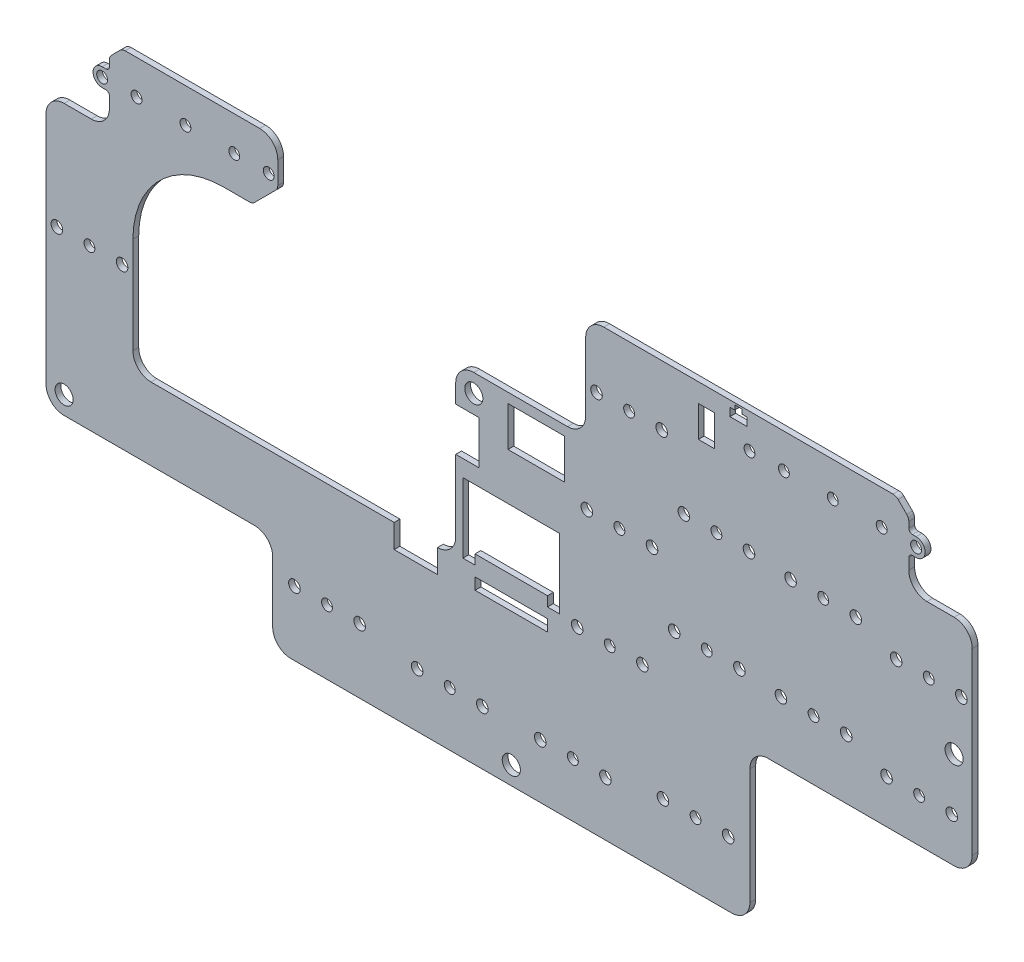
SolidWorks part; units mm, degrees
ref_plane "Front Plane" through (0, 0, 0) normal (0, 0, 1) x (1, 0, 0)
ref_plane "Top Plane" through (0, 0, 0) normal (0, 1, 0) x (1, 0, 0)
ref_plane "Right Plane" through (0, 0, 0) normal (1, 0, 0) x (0, 0, -1)
sketch "Sketch1" plane through (0, 0, 0) normal (0, 0, 1) x (1, 0, 0)
  line L0 (157.8919, 26.2701) -> (191.7747, 29.0915)
  line L1 (157.8919, 26.2701) -> (191.7747, 26.2701)
  line L2 (157.8919, 26.2701) -> (157.8919, 29.0915)
  line L3 (157.8919, 29.0915) -> (191.7747, 29.0915)
  line L4 (191.7747, 26.2701) -> (191.7747, 29.0915)
  line L5 (123.8919, 26.2701) -> (90.0092, 26.2701)
  line L6 (123.8919, 26.2701) -> (123.8919, 29.0915)
  line L7 (123.8919, 29.0915) -> (90.0092, 29.0915)
  line L8 (90.0092, 26.2701) -> (90.0092, 29.0915)
  line L9 (90.0092, 29.0915) -> (123.8919, 26.2701)
  line L10 (168.0919, 58.3601) -> (194.8735, 70.7292)
  line L11 (168.0919, 58.3601) -> (194.8735, 58.3601)
  line L12 (168.0919, 58.3601) -> (168.0919, 70.7292)
  line L13 (168.0919, 70.7292) -> (194.8735, 70.7292)
  line L14 (194.8735, 58.3601) -> (194.8735, 70.7292)
  line L15 (194.8735, 70.7292) -> (224.3587, 70.7292)
  line L16 (194.8735, 70.7292) -> (194.8735, 69.7923)
  line L17 (194.8735, 69.7923) -> (224.3587, 69.7923)
  line L18 (224.3587, 70.7292) -> (224.3587, 69.7923)
  line L19 (224.3587, 69.7923) -> (253.5106, 69.7923)
  line L20 (224.3587, 69.7923) -> (224.3587, 65.2742)
  line L21 (224.3587, 65.2742) -> (253.5106, 65.2742)
  line L22 (253.5106, 69.7923) -> (253.5106, 65.2742)
  line L23 (224.3587, 69.7923) -> (194.8735, 70.7292)
  line L24 (253.5106, 65.2742) -> (224.3587, 69.7923)
  line L25 (170.7502, 87.7401) -> (168.0919, 58.3601)
  line L26 (168.0919, 58.3601) -> (170.7502, 58.3601)
  line L27 (168.0919, 58.3601) -> (168.0919, 87.7401)
  line L28 (168.0919, 87.7401) -> (170.7502, 87.7401)
  line L29 (170.7502, 58.3601) -> (170.7502, 87.7401)
  line L30 (52.9966, 89.4705) -> (24.4119, 82.1791)
  line L31 (24.4119, 82.1791) -> (52.9966, 82.1791)
  line L32 (24.4119, 82.1791) -> (24.4119, 89.4705)
  line L33 (24.4119, 89.4705) -> (52.9966, 89.4705)
  line L34 (52.9966, 82.1791) -> (52.9966, 89.4705)
  line L35 (82.4966, 89.4705) -> (109.0019, 89.4705)
  line L36 (82.4966, 89.4705) -> (82.4966, 76.5201)
  line L37 (82.4966, 76.5201) -> (109.0019, 76.5201)
  line L38 (109.0019, 89.4705) -> (109.0019, 76.5201)
  line L39 (92.4554, 117.2387) -> (82.4966, 117.2387)
  line L40 (92.4554, 117.2387) -> (92.4554, 89.4705)
  line L41 (92.4554, 89.4705) -> (82.4966, 89.4705)
  line L42 (82.4966, 117.2387) -> (82.4966, 89.4705)
  line L43 (92.4554, 117.2387) -> (82.4966, 89.4705)
  line L44 (109.0019, 76.5201) -> (82.4966, 89.4705)
  circle A0 centre (123.8919, 26.2701) radius 14.25
  circle A1 centre (157.8919, 26.2701) radius 14.25
  circle A2 centre (90.0092, 29.0915) radius 14.25
  circle A3 centre (191.7747, 29.0915) radius 14.25
  circle A4 centre (82.4966, 89.4705) radius 11.25
  circle A5 centre (92.4554, 117.2387) radius 11.25
  circle A6 centre (52.9966, 89.4705) radius 11.25
  circle A7 centre (109.0019, 76.5201) radius 11.25
  circle A8 centre (24.4119, 82.1791) radius 11.25
  circle A9 centre (170.7502, 87.7401) radius 11.25
  circle A10 centre (168.0919, 58.3601) radius 11.25
  circle A11 centre (197.5318, 100.1092) radius 11.25
  circle A12 centre (194.8735, 70.7292) radius 11.25
  circle A13 centre (227.0169, 99.1723) radius 11.25
  circle A14 centre (224.3587, 69.7923) radius 11.25
  circle A15 centre (256.1689, 94.6541) radius 11.25
  circle A16 centre (253.5106, 65.2742) radius 11.25
  circle A17 centre (24.4119, 82.1791) radius 12
  circle A18 centre (52.9966, 89.4705) radius 12
  circle A19 centre (92.4554, 117.2387) radius 12
  circle A20 centre (82.4966, 89.4705) radius 12
  circle A21 centre (109.0019, 76.5201) radius 12
  circle A22 centre (168.0919, 58.3601) radius 12
  circle A23 centre (194.8735, 70.7292) radius 12
  circle A24 centre (224.3587, 69.7923) radius 12
  circle A25 centre (253.5106, 65.2742) radius 12
  circle A26 centre (256.1689, 94.6541) radius 12
  circle A27 centre (227.0169, 99.1723) radius 12
  circle A28 centre (197.5318, 100.1092) radius 12
  circle A29 centre (170.7502, 87.7401) radius 12
  circle A30 centre (191.7747, 29.0915) radius 15
  circle A31 centre (157.8919, 26.2701) radius 15
  circle A32 centre (123.8919, 26.2701) radius 15
  circle A33 centre (90.0092, 29.0915) radius 15
  circle A34 centre (173.429, 117.1182) radius 11.25
  circle A35 centre (173.429, 117.1182) radius 12
  dimension "D1" = 28.5
  dimension "D2" = 22.5
  dimension "D3" = 0.75
  dimension "D4" = 0.75
  dimension "D34" = 34
  dimension "D5" = 29.5
  dimension "D6" = 29.5
  dimension "D7" = 29.5
  dimension "D8" = 29.5
  dimension "D9" = 29.5
  dimension "D10" = 29.5
  dimension "D11" = 29.5
  dimension "D12" = 29.5
  dimension "D13" = 29.5
  dimension "D14" = 29.5
  dimension "D15" = 29.5
  dimension "D16" = 29.5
  dimension "D17" = 29.5
  dimension "D18" = 29.5
  dimension "D19" = 34
  dimension "D20" = 34
  dimension "D21" = 32.09
  dimension "D22" = 10.2
  dimension "D23" = 4.76
  dimension "D24" = 4.76
  dimension "D25" = 24.79
  dimension "D26" = 1.82
  dimension "D27" = 8.81
  dimension "D28" = 84.83
  dimension "D29" = 75.69
  dimension "D30" = 70.27
  dimension "D31" = 26.04
  dimension "D32" = 14.89
  dimension "D33" = 50.25
  dimension "D35" = 29.5
  dimension "D36" = 29.5
sketch "Sketch4" plane through (-30.2083, 20.075, 0) normal (0, 0, 1) x (0.9781, -0.2079, 0)
  line L0 (86.1706, 94.1917) -> (105.2206, 75.1417)
  line L1 (67.1206, 94.1917) -> (86.1706, 94.1917)
  line L2 (67.1206, 94.1917) -> (67.1206, 75.1417)
  line L3 (67.1206, 75.1417) -> (86.1706, 75.1417)
  line L4 (86.1706, 94.1917) -> (86.1706, 75.1417)
  line L5 (86.1706, 94.1917) -> (105.2206, 94.1917)
  line L6 (86.1706, 94.1917) -> (86.1706, 75.1417)
  line L7 (86.1706, 75.1417) -> (105.2206, 75.1417)
  line L8 (105.2206, 94.1917) -> (105.2206, 75.1417)
  line L9 (105.2206, 94.1917) -> (124.2706, 94.1917)
  line L10 (105.2206, 94.1917) -> (105.2206, 75.1417)
  line L11 (105.2206, 75.1417) -> (124.2706, 75.1417)
  line L12 (124.2706, 94.1917) -> (124.2706, 75.1417)
  line L13 (86.1706, 94.1917) -> (105.2206, 94.1917)
  line L14 (86.1706, 94.1917) -> (86.1706, 113.2417)
  line L15 (86.1706, 113.2417) -> (105.2206, 113.2417)
  line L16 (105.2206, 94.1917) -> (105.2206, 113.2417)
  line L17 (66.9585, 85.1784) -> (124.4326, 84.1551)
  point P14 (95.6956, 84.6667)
  point P15 (95.6956, 84.6667)
  dimension "D1" = 19.05
sketch "Sketch9" plane through (0, 0, 0) normal (0, 0, 1) x (1, 0, 0)
  line L1 (17.3619, 89.2291) -> (31.4619, 89.2291)
  line L2 (17.3619, 89.2291) -> (17.3619, 75.1291)
  line L3 (17.3619, 75.1291) -> (31.4619, 75.1291)
  line L4 (31.4619, 89.2291) -> (31.4619, 75.1291)
  line L5 (45.9466, 96.5205) -> (60.0466, 96.5205)
  line L6 (45.9466, 96.5205) -> (45.9466, 82.4205)
  line L7 (45.9466, 82.4205) -> (60.0466, 82.4205)
  line L8 (60.0466, 96.5205) -> (60.0466, 82.4205)
  line L9 (75.4466, 96.5205) -> (89.5466, 96.5205)
  line L10 (75.4466, 96.5205) -> (75.4466, 82.4205)
  line L11 (75.4466, 82.4205) -> (89.5466, 82.4205)
  line L12 (89.5466, 96.5205) -> (89.5466, 82.4205)
  line L13 (101.9519, 83.5701) -> (116.0519, 83.5701)
  line L14 (101.9519, 83.5701) -> (101.9519, 69.4701)
  line L15 (101.9519, 69.4701) -> (116.0519, 69.4701)
  line L16 (116.0519, 83.5701) -> (116.0519, 69.4701)
  line L17 (85.4054, 124.2887) -> (99.5054, 124.2887)
  line L18 (85.4054, 124.2887) -> (85.4054, 110.1887)
  line L19 (85.4054, 110.1887) -> (99.5054, 110.1887)
  line L20 (99.5054, 124.2887) -> (99.5054, 110.1887)
  line L21 (82.9592, 36.1415) -> (97.0592, 36.1415)
  line L22 (82.9592, 36.1415) -> (82.9592, 22.0415)
  line L23 (82.9592, 22.0415) -> (97.0592, 22.0415)
  line L24 (97.0592, 36.1415) -> (97.0592, 22.0415)
  line L25 (116.8419, 33.3201) -> (130.9419, 33.3201)
  line L26 (116.8419, 33.3201) -> (116.8419, 19.2201)
  line L27 (116.8419, 19.2201) -> (130.9419, 19.2201)
  line L28 (130.9419, 33.3201) -> (130.9419, 19.2201)
  line L29 (150.8419, 33.3201) -> (164.9419, 33.3201)
  line L30 (150.8419, 33.3201) -> (150.8419, 19.2201)
  line L31 (150.8419, 19.2201) -> (164.9419, 19.2201)
  line L32 (164.9419, 33.3201) -> (164.9419, 19.2201)
  line L33 (184.7247, 36.1415) -> (198.8247, 36.1415)
  line L34 (184.7247, 36.1415) -> (184.7247, 22.0415)
  line L35 (184.7247, 22.0415) -> (198.8247, 22.0415)
  line L36 (198.8247, 36.1415) -> (198.8247, 22.0415)
  line L37 (260.5606, 58.2242) -> (246.4606, 58.2242)
  line L38 (260.5606, 58.2242) -> (260.5606, 72.3242)
  line L39 (260.5606, 72.3242) -> (246.4606, 72.3242)
  line L40 (246.4606, 58.2242) -> (246.4606, 72.3242)
  line L41 (217.3087, 76.8423) -> (231.4087, 76.8423)
  line L42 (217.3087, 76.8423) -> (217.3087, 62.7423)
  line L43 (217.3087, 62.7423) -> (231.4087, 62.7423)
  line L44 (231.4087, 76.8423) -> (231.4087, 62.7423)
  line L45 (187.8235, 77.7792) -> (201.9235, 77.7792)
  line L46 (187.8235, 77.7792) -> (187.8235, 63.6792)
  line L47 (187.8235, 63.6792) -> (201.9235, 63.6792)
  line L48 (201.9235, 77.7792) -> (201.9235, 63.6792)
  line L49 (161.0419, 65.4101) -> (175.1419, 65.4101)
  line L50 (161.0419, 65.4101) -> (161.0419, 51.3101)
  line L51 (161.0419, 51.3101) -> (175.1419, 51.3101)
  line L52 (175.1419, 65.4101) -> (175.1419, 51.3101)
  line L53 (163.7002, 94.7901) -> (177.8002, 94.7901)
  line L54 (163.7002, 94.7901) -> (163.7002, 80.6901)
  line L55 (163.7002, 80.6901) -> (177.8002, 80.6901)
  line L56 (177.8002, 94.7901) -> (177.8002, 80.6901)
  line L57 (190.4818, 107.1592) -> (204.5818, 107.1592)
  line L58 (190.4818, 107.1592) -> (190.4818, 93.0592)
  line L59 (190.4818, 93.0592) -> (204.5818, 93.0592)
  line L60 (204.5818, 107.1592) -> (204.5818, 93.0592)
  line L61 (219.9669, 106.2223) -> (234.0669, 106.2223)
  line L62 (219.9669, 106.2223) -> (219.9669, 92.1223)
  line L63 (219.9669, 92.1223) -> (234.0669, 92.1223)
  line L64 (234.0669, 106.2223) -> (234.0669, 92.1223)
  line L65 (249.1189, 101.7041) -> (263.2189, 101.7041)
  line L66 (249.1189, 101.7041) -> (249.1189, 87.6041)
  line L67 (249.1189, 87.6041) -> (263.2189, 87.6041)
  line L68 (263.2189, 101.7041) -> (263.2189, 87.6041)
  line L69 (166.379, 124.1682) -> (180.479, 124.1682)
  line L70 (166.379, 124.1682) -> (166.379, 110.0682)
  line L71 (166.379, 110.0682) -> (180.479, 110.0682)
  line L72 (180.479, 124.1682) -> (180.479, 110.0682)
  point P72 (24.4119, 89.2291)
  point P74 (52.9966, 96.5205)
  point P76 (82.4966, 96.5205)
  point P78 (92.4554, 124.2887)
  point P80 (109.0019, 83.5701)
  point P82 (90.0092, 36.1415)
  point P84 (123.8919, 33.3201)
  point P86 (157.8919, 33.3201)
  point P88 (191.7747, 36.1415)
  point P90 (168.0919, 65.4101)
  point P92 (170.7502, 94.7901)
  point P94 (173.429, 124.1682)
  point P96 (197.5318, 107.1592)
  point P98 (227.0169, 106.2223)
  point P100 (256.1689, 101.7041)
  point P102 (194.8735, 77.7792)
  point P104 (224.3587, 76.8423)
  point P106 (253.5106, 72.3242)
  point P108 (17.3619, 82.1791)
  point P109 (45.9466, 89.4705)
  point P110 (75.4466, 89.4705)
  point P111 (101.9519, 76.5201)
  point P112 (85.4054, 117.2387)
  point P113 (82.9592, 29.0915)
  point P114 (116.8419, 26.2701)
  point P115 (150.8419, 26.2701)
  point P116 (184.7247, 29.0915)
  point P118 (161.0419, 58.3601)
  point P119 (187.8235, 70.7292)
  point P120 (217.3087, 69.7923)
  point P121 (246.4606, 65.2742)
  point P122 (163.7002, 87.7401)
  point P123 (190.4818, 100.1092)
  point P124 (219.9669, 99.1723)
  point P125 (249.1189, 94.6541)
  point P126 (166.379, 117.1182)
  dimension "D1" = 14.1
sketch "Sketch10" plane through (-22.0981, 19.3454, 0) normal (0, 0, 1) x (0.9781, -0.2079, 0)
  line L1 (61.5108, 90.7441) -> (75.6108, 90.7441)
  line L2 (61.5108, 90.7441) -> (61.5108, 76.6441)
  line L3 (61.5108, 76.6441) -> (75.6108, 76.6441)
  line L4 (75.6108, 90.7441) -> (75.6108, 76.6441)
  line L5 (80.5608, 90.7441) -> (94.6608, 90.7441)
  line L6 (80.5608, 90.7441) -> (80.5608, 76.6441)
  line L7 (80.5608, 76.6441) -> (94.6608, 76.6441)
  line L8 (94.6608, 90.7441) -> (94.6608, 76.6441)
  line L9 (99.6108, 90.7441) -> (113.7108, 90.7441)
  line L10 (99.6108, 90.7441) -> (99.6108, 76.6441)
  line L11 (99.6108, 76.6441) -> (113.7108, 76.6441)
  line L12 (113.7108, 90.7441) -> (113.7108, 76.6441)
  line L13 (80.5608, 109.7941) -> (94.6608, 109.7941)
  line L14 (80.5608, 109.7941) -> (80.5608, 95.6941)
  line L15 (80.5608, 95.6941) -> (94.6608, 95.6941)
  line L16 (94.6608, 109.7941) -> (94.6608, 95.6941)
  line L17 (50.5121, 89.6359) -> (53.4436, 75.8441) construction
  line L18 (59.0358, 93.2191) -> (78.0858, 93.2191) construction
  line L19 (78.0858, 112.2691) -> (97.1358, 112.2691) construction
  line L20 (97.1358, 93.2191) -> (116.1858, 93.2191) construction
  line L21 (78.0858, 93.2191) -> (78.0858, 112.2691) construction
  line L23 (59.0358, 93.2191) -> (59.0358, 74.1691) construction
  point P16 (75.6108, 83.6941)
  point P17 (94.6608, 83.6941)
  point P18 (113.7108, 83.6941)
  point P19 (87.6108, 90.7441)
  point P20 (87.6108, 109.7941)
  point P23 (68.5608, 90.7441)
  point P26 (68.5608, 93.2191)
  point P29 (87.6108, 112.2691)
  point P30 (106.6608, 90.7441)
  point P33 (106.6608, 93.2191)
  point P34 (80.5608, 102.7441)
  point P37 (78.0858, 102.7441)
  point P42 (59.0358, 83.6941)
  point P43 (61.5108, 83.6941)
sketch "Sketch14" plane through (0, 0, 0) normal (0, 0, 1) x (1, 0, 0)
  line L0 (165.1144, 80.6901) -> (163.7002, 82.1043)
  line L1 (163.7002, 93.3758) -> (165.1144, 94.7901)
  line L2 (177.8002, 93.3758) -> (176.386, 94.7901)
  line L3 (179.0648, 110.0682) -> (180.479, 111.4824)
  line L4 (166.379, 111.4824) -> (167.7932, 110.0682)
  line L5 (166.379, 122.754) -> (167.7932, 124.1682)
  line L6 (179.0648, 124.1682) -> (180.479, 122.754)
  line L7 (203.1676, 93.0592) -> (204.5818, 94.4734)
  line L8 (17.3619, 89.2291) -> (17.3619, 75.1291) construction
  line L9 (17.3619, 89.2291) -> (31.4619, 89.2291) construction
  line L10 (17.3619, 87.8149) -> (18.7761, 89.2291)
  line L11 (17.3619, 75.1291) -> (31.4619, 75.1291) construction
  line L12 (31.4619, 89.2291) -> (31.4619, 75.1291) construction
  line L13 (45.9466, 96.5205) -> (60.0466, 96.5205) construction
  line L14 (60.0466, 96.5205) -> (60.0466, 82.4205) construction
  line L15 (45.9466, 96.5205) -> (45.9466, 82.4205) construction
  line L16 (45.9466, 82.4205) -> (60.0466, 82.4205) construction
  line L17 (85.4054, 124.2887) -> (85.4054, 110.1887) construction
  line L18 (85.4054, 124.2887) -> (99.5054, 124.2887) construction
  line L19 (99.5054, 124.2887) -> (99.5054, 110.1887) construction
  line L20 (85.4054, 110.1887) -> (99.5054, 110.1887) construction
  line L21 (101.9519, 83.5701) -> (101.9519, 69.4701) construction
  line L22 (101.9519, 83.5701) -> (116.0519, 83.5701) construction
  line L23 (116.0519, 83.5701) -> (116.0519, 69.4701) construction
  line L24 (101.9519, 69.4701) -> (116.0519, 69.4701) construction
  line L25 (91.2712, 73.6044) -> (105.0631, 70.6729) construction
  line L26 (107.9947, 84.4647) -> (105.0631, 70.6729) construction
  line L27 (94.2028, 87.3963) -> (107.9947, 84.4647) construction
  line L28 (94.2028, 87.3963) -> (91.2712, 73.6044) construction
  line L29 (72.6375, 77.5651) -> (86.4294, 74.6336) construction
  line L30 (89.361, 88.4255) -> (86.4294, 74.6336) construction
  line L31 (75.5691, 91.357) -> (89.361, 88.4255) construction
  line L32 (75.5691, 91.357) -> (72.6375, 77.5651) construction
  line L33 (56.9354, 95.3177) -> (54.0038, 81.5259) construction
  line L34 (56.9354, 95.3177) -> (70.7273, 92.3862) construction
  line L35 (70.7273, 92.3862) -> (67.7957, 78.5943) construction
  line L36 (54.0038, 81.5259) -> (67.7957, 78.5943) construction
  line L37 (76.5983, 96.1988) -> (90.3901, 93.2673) construction
  line L38 (93.3217, 107.0592) -> (90.3901, 93.2673) construction
  line L39 (79.5298, 109.9907) -> (76.5983, 96.1988) construction
  line L40 (79.5298, 109.9907) -> (93.3217, 107.0592) construction
  line L41 (82.9592, 36.1415) -> (82.9592, 22.0415) construction
  line L42 (82.9592, 36.1415) -> (97.0592, 36.1415) construction
  line L43 (82.9592, 22.0415) -> (97.0592, 22.0415) construction
  line L44 (97.0592, 36.1415) -> (97.0592, 22.0415) construction
  line L45 (116.8419, 33.3201) -> (116.8419, 19.2201) construction
  line L46 (116.8419, 33.3201) -> (130.9419, 33.3201) construction
  line L47 (116.8419, 19.2201) -> (130.9419, 19.2201) construction
  line L48 (130.9419, 33.3201) -> (130.9419, 19.2201) construction
  line L49 (150.8419, 33.3201) -> (150.8419, 19.2201) construction
  line L50 (150.8419, 33.3201) -> (164.9419, 33.3201) construction
  line L51 (164.9419, 33.3201) -> (164.9419, 19.2201) construction
  line L52 (150.8419, 19.2201) -> (164.9419, 19.2201) construction
  line L53 (184.7247, 36.1415) -> (184.7247, 22.0415) construction
  line L54 (184.7247, 22.0415) -> (198.8247, 22.0415) construction
  line L55 (198.8247, 36.1415) -> (198.8247, 22.0415) construction
  line L56 (184.7247, 36.1415) -> (198.8247, 36.1415) construction
  line L57 (161.0419, 65.4101) -> (175.1419, 65.4101) construction
  line L58 (175.1419, 65.4101) -> (175.1419, 51.3101) construction
  line L59 (161.0419, 51.3101) -> (175.1419, 51.3101) construction
  line L60 (161.0419, 65.4101) -> (161.0419, 51.3101) construction
  line L61 (187.8235, 77.7792) -> (187.8235, 63.6792) construction
  line L62 (187.8235, 77.7792) -> (201.9235, 77.7792) construction
  line L63 (187.8235, 63.6792) -> (201.9235, 63.6792) construction
  line L64 (201.9235, 77.7792) -> (201.9235, 63.6792) construction
  line L65 (217.3087, 76.8423) -> (217.3087, 62.7423) construction
  line L66 (217.3087, 76.8423) -> (231.4087, 76.8423) construction
  line L67 (231.4087, 76.8423) -> (231.4087, 62.7423) construction
  line L68 (217.3087, 62.7423) -> (231.4087, 62.7423) construction
  line L69 (260.5606, 58.2242) -> (246.4606, 58.2242) construction
  line L70 (260.5606, 58.2242) -> (260.5606, 72.3242) construction
  line L71 (246.4606, 58.2242) -> (246.4606, 72.3242) construction
  line L72 (260.5606, 72.3242) -> (246.4606, 72.3242) construction
  line L73 (249.1189, 101.7041) -> (263.2189, 101.7041) construction
  line L74 (263.2189, 101.7041) -> (263.2189, 87.6041) construction
  line L75 (249.1189, 87.6041) -> (263.2189, 87.6041) construction
  line L76 (249.1189, 101.7041) -> (249.1189, 87.6041) construction
  line L77 (219.9669, 106.2223) -> (219.9669, 92.1223) construction
  line L78 (219.9669, 106.2223) -> (234.0669, 106.2223) construction
  line L79 (234.0669, 106.2223) -> (234.0669, 92.1223) construction
  line L80 (219.9669, 92.1223) -> (234.0669, 92.1223) construction
  line L81 (190.4818, 107.1592) -> (204.5818, 107.1592) construction
  line L82 (204.5818, 107.1592) -> (204.5818, 93.0592) construction
  line L83 (190.4818, 93.0592) -> (204.5818, 93.0592) construction
  line L84 (190.4818, 107.1592) -> (190.4818, 93.0592) construction
  line L85 (163.7002, 94.7901) -> (177.8002, 94.7901) construction
  line L86 (177.8002, 94.7901) -> (177.8002, 80.6901) construction
  line L87 (163.7002, 80.6901) -> (177.8002, 80.6901) construction
  line L88 (163.7002, 94.7901) -> (163.7002, 80.6901) construction
  line L89 (180.479, 124.1682) -> (180.479, 110.0682) construction
  line L90 (166.379, 110.0682) -> (180.479, 110.0682) construction
  line L91 (166.379, 124.1682) -> (166.379, 110.0682) construction
  line L92 (166.379, 124.1682) -> (180.479, 124.1682) construction
  line L93 (17.3619, 76.5433) -> (18.7761, 75.1291)
  line L94 (30.0477, 75.1291) -> (31.4619, 76.5433)
  line L95 (31.4619, 87.8149) -> (30.0477, 89.2291)
  line L96 (45.9466, 95.1063) -> (47.3608, 96.5205)
  line L97 (45.9466, 83.8347) -> (47.3608, 82.4205)
  line L98 (54.2979, 82.9092) -> (55.3871, 81.2318)
  line L99 (58.6323, 82.4205) -> (60.0466, 83.8347)
  line L100 (56.6413, 93.9344) -> (58.3187, 95.0237)
  line L101 (58.6323, 96.5205) -> (60.0466, 95.1063)
  line L102 (69.3439, 92.6802) -> (70.4332, 91.0029)
  line L103 (68.0897, 79.9776) -> (66.4124, 78.8883)
  line L104 (75.2751, 89.9737) -> (76.9524, 91.063)
  line L105 (72.9316, 78.9484) -> (74.0208, 77.2711)
  line L106 (85.0461, 74.9276) -> (86.7234, 76.0169)
  line L107 (89.0669, 87.0421) -> (87.9777, 88.7195)
  line L108 (89.0068, 93.5613) -> (90.6842, 94.6506)
  line L109 (76.8923, 97.5822) -> (77.9816, 95.9048)
  line L110 (91.9384, 107.3532) -> (93.0277, 105.6759)
  line L111 (79.2358, 108.6074) -> (80.9131, 109.6967)
  line L112 (85.4054, 111.6029) -> (86.8196, 110.1887)
  line L113 (98.0912, 110.1887) -> (99.5054, 111.6029)
  line L114 (98.0912, 124.2887) -> (99.5054, 122.8745)
  line L115 (85.4054, 122.8745) -> (86.8196, 124.2887)
  line L116 (93.9088, 86.013) -> (95.5861, 87.1023)
  line L117 (91.5653, 74.9877) -> (92.6546, 73.3104)
  line L118 (103.6798, 70.9669) -> (105.3572, 72.0562)
  line L119 (106.6114, 84.7588) -> (107.7006, 83.0814)
  line L120 (101.9519, 82.1559) -> (103.3662, 83.5701)
  line L121 (101.9519, 70.8843) -> (103.3662, 69.4701)
  line L122 (114.6377, 69.4701) -> (116.0519, 70.8843)
  line L123 (116.0519, 82.1559) -> (114.6377, 83.5701)
  line L124 (82.9592, 34.7272) -> (84.3734, 36.1415)
  line L125 (82.9592, 23.4557) -> (84.3734, 22.0415)
  line L126 (95.645, 22.0415) -> (97.0592, 23.4557)
  line L127 (97.0592, 34.7272) -> (95.645, 36.1415)
  line L128 (116.8419, 31.9059) -> (118.2562, 33.3201)
  line L129 (116.8419, 20.6343) -> (118.2562, 19.2201)
  line L130 (129.5277, 19.2201) -> (130.9419, 20.6343)
  line L131 (130.9419, 31.9059) -> (129.5277, 33.3201)
  line L132 (150.8419, 31.9059) -> (152.2562, 33.3201)
  line L133 (150.8419, 20.6343) -> (152.2562, 19.2201)
  line L134 (163.5277, 19.2201) -> (164.9419, 20.6343)
  line L135 (164.9419, 31.9059) -> (163.5277, 33.3201)
  line L136 (184.7247, 34.7272) -> (186.1389, 36.1415)
  line L137 (184.7247, 23.4557) -> (186.1389, 22.0415)
  line L138 (197.4105, 22.0415) -> (198.8247, 23.4557)
  line L139 (198.8247, 34.7272) -> (197.4105, 36.1415)
  line L140 (173.7277, 51.3101) -> (175.1419, 52.7243)
  line L141 (161.0419, 52.7243) -> (162.4562, 51.3101)
  line L142 (161.0419, 63.9959) -> (162.4562, 65.4101)
  line L143 (173.7277, 65.4101) -> (175.1419, 63.9959)
  line L144 (187.8235, 65.0934) -> (189.2378, 63.6792)
  line L145 (200.5093, 63.6792) -> (201.9235, 65.0934)
  line L146 (200.5093, 77.7792) -> (201.9235, 76.365)
  line L147 (187.8235, 76.365) -> (189.2378, 77.7792)
  line L148 (176.386, 80.6901) -> (177.8002, 82.1043)
  line L149 (204.5818, 105.745) -> (203.1676, 107.1592)
  line L150 (191.896, 107.1592) -> (190.4818, 105.745)
  line L151 (190.4818, 94.4734) -> (191.896, 93.0592)
  line L152 (219.9669, 104.8081) -> (221.3812, 106.2223)
  line L153 (232.6527, 106.2223) -> (234.0669, 104.8081)
  line L154 (234.0669, 93.5365) -> (232.6527, 92.1223)
  line L155 (219.9669, 93.5365) -> (221.3812, 92.1223)
  line L156 (229.9944, 76.8423) -> (231.4087, 75.4281)
  line L157 (217.3087, 75.4281) -> (218.7229, 76.8423)
  line L158 (217.3087, 64.1565) -> (218.7229, 62.7423)
  line L159 (229.9944, 62.7423) -> (231.4087, 64.1565)
  line L160 (259.1464, 72.3242) -> (260.5606, 70.9099)
  line L161 (246.4606, 70.9099) -> (247.8748, 72.3242)
  line L162 (259.1464, 58.2242) -> (260.5606, 59.6384)
  line L163 (247.8748, 58.2242) -> (246.4606, 59.6384)
  line L164 (261.8047, 87.6041) -> (263.2189, 89.0183)
  line L165 (249.1189, 89.0183) -> (250.5331, 87.6041)
  line L166 (249.1189, 100.2899) -> (250.5331, 101.7041)
  line L167 (261.8047, 101.7041) -> (263.2189, 100.2899)
  line L168 (75.4466, 96.5205) -> (75.4466, 82.4205) construction
  line L169 (75.4466, 96.5205) -> (89.5466, 96.5205) construction
  line L170 (89.5466, 96.5205) -> (89.5466, 82.4205) construction
  line L171 (75.4466, 82.4205) -> (89.5466, 82.4205) construction
  line L172 (76.8608, 96.5205) -> (75.4466, 95.1063)
  line L173 (88.1323, 96.5205) -> (89.5466, 95.1063)
  line L174 (89.5466, 83.8347) -> (88.1323, 82.4205)
  line L175 (75.4466, 83.8347) -> (76.8608, 82.4205)
  arc A0 (17.3619, 87.8149) -> (18.7761, 89.2291) centre (18.069, 88.522) cw
  arc A1 (18.7761, 75.1291) -> (17.3619, 76.5433) centre (18.069, 75.8362) cw
  arc A2 (31.4619, 76.5433) -> (30.0477, 75.1291) centre (30.7548, 75.8362) cw
  arc A3 (30.0477, 89.2291) -> (31.4619, 87.8149) centre (30.7548, 88.522) cw
  arc A4 (58.6323, 96.5205) -> (60.0466, 95.1063) centre (59.3394, 95.8134) cw
  arc A5 (45.9466, 95.1063) -> (47.3608, 96.5205) centre (46.6537, 95.8134) cw
  arc A6 (47.3608, 82.4205) -> (45.9466, 83.8347) centre (46.6537, 83.1276) cw
  arc A7 (60.0466, 83.8347) -> (58.6323, 82.4205) centre (59.3394, 83.1276) cw
  arc A8 (85.4054, 122.8745) -> (86.8196, 124.2887) centre (86.1125, 123.5816) cw
  arc A9 (98.0912, 124.2887) -> (99.5054, 122.8745) centre (98.7983, 123.5816) cw
  arc A10 (99.5054, 111.6029) -> (98.0912, 110.1887) centre (98.7983, 110.8958) cw
  arc A11 (85.4054, 111.6029) -> (86.8196, 110.1887) centre (86.1125, 110.8958) ccw
  arc A12 (101.9519, 82.1559) -> (103.3662, 83.5701) centre (102.6591, 82.863) cw
  arc A13 (114.6377, 83.5701) -> (116.0519, 82.1559) centre (115.3448, 82.863) cw
  arc A14 (116.0519, 70.8843) -> (114.6377, 69.4701) centre (115.3448, 70.1772) cw
  arc A15 (101.9519, 70.8843) -> (103.3662, 69.4701) centre (102.6591, 70.1772) ccw
  arc A16 (103.6798, 70.9669) -> (105.3572, 72.0562) centre (104.5185, 71.5115) ccw
  arc A17 (106.6114, 84.7588) -> (107.7006, 83.0814) centre (107.156, 83.9201) cw
  arc A18 (93.9088, 86.013) -> (95.5861, 87.1023) centre (94.7474, 86.5576) cw
  arc A19 (91.5653, 74.9877) -> (92.6546, 73.3104) centre (92.1099, 74.1491) ccw
  arc A20 (85.0461, 74.9276) -> (86.7234, 76.0169) centre (85.8848, 75.4722) ccw
  arc A21 (87.9777, 88.7195) -> (89.0669, 87.0421) centre (88.5223, 87.8808) cw
  arc A22 (75.2751, 89.9737) -> (76.9524, 91.063) centre (76.1137, 90.5183) cw
  arc A23 (72.9316, 78.9484) -> (74.0208, 77.2711) centre (73.4762, 78.1098) ccw
  arc A24 (56.6413, 93.9344) -> (58.3187, 95.0237) centre (57.48, 94.4791) cw
  arc A25 (69.3439, 92.6802) -> (70.4332, 91.0029) centre (69.8886, 91.8415) cw
  arc A26 (68.0897, 79.9776) -> (66.4124, 78.8883) centre (67.2511, 79.433) cw
  arc A27 (54.2979, 82.9092) -> (55.3871, 81.2318) centre (54.8425, 82.0705) ccw
  arc A28 (89.0068, 93.5613) -> (90.6842, 94.6506) centre (89.8455, 94.106) ccw
  arc A29 (76.8923, 97.5822) -> (77.9816, 95.9048) centre (77.4369, 96.7435) ccw
  arc A30 (79.2358, 108.6074) -> (80.9131, 109.6967) centre (80.0744, 109.1521) cw
  arc A31 (91.9384, 107.3532) -> (93.0277, 105.6759) centre (92.483, 106.5145) cw
  arc A32 (82.9592, 34.7272) -> (84.3734, 36.1415) centre (83.6663, 35.4344) cw
  arc A33 (82.9592, 23.4557) -> (84.3734, 22.0415) centre (83.6663, 22.7486) ccw
  arc A34 (95.645, 22.0415) -> (97.0592, 23.4557) centre (96.3521, 22.7486) ccw
  arc A35 (95.645, 36.1415) -> (97.0592, 34.7272) centre (96.3521, 35.4344) cw
  arc A36 (116.8419, 31.9059) -> (118.2562, 33.3201) centre (117.5491, 32.613) cw
  arc A37 (116.8419, 20.6343) -> (118.2562, 19.2201) centre (117.5491, 19.9272) ccw
  arc A38 (129.5277, 19.2201) -> (130.9419, 20.6343) centre (130.2348, 19.9272) ccw
  arc A39 (129.5277, 33.3201) -> (130.9419, 31.9059) centre (130.2348, 32.613) cw
  arc A40 (150.8419, 31.9059) -> (152.2562, 33.3201) centre (151.5491, 32.613) cw
  arc A41 (163.5277, 33.3201) -> (164.9419, 31.9059) centre (164.2348, 32.613) cw
  arc A42 (164.9419, 20.6343) -> (163.5277, 19.2201) centre (164.2348, 19.9272) cw
  arc A43 (150.8419, 20.6343) -> (152.2562, 19.2201) centre (151.5491, 19.9272) ccw
  arc A44 (184.7247, 23.4557) -> (186.1389, 22.0415) centre (185.4318, 22.7486) ccw
  arc A45 (197.4105, 22.0415) -> (198.8247, 23.4557) centre (198.1176, 22.7486) ccw
  arc A46 (197.4105, 36.1415) -> (198.8247, 34.7272) centre (198.1176, 35.4344) cw
  arc A47 (184.7247, 34.7272) -> (186.1389, 36.1415) centre (185.4318, 35.4344) cw
  arc A48 (173.7277, 65.4101) -> (175.1419, 63.9959) centre (174.4348, 64.703) cw
  arc A49 (175.1419, 52.7243) -> (173.7277, 51.3101) centre (174.4348, 52.0172) cw
  arc A50 (161.0419, 52.7243) -> (162.4562, 51.3101) centre (161.7491, 52.0172) ccw
  arc A51 (161.0419, 63.9959) -> (162.4562, 65.4101) centre (161.7491, 64.703) cw
  arc A52 (187.8235, 76.365) -> (189.2378, 77.7792) centre (188.5306, 77.0721) cw
  arc A53 (187.8235, 65.0934) -> (189.2378, 63.6792) centre (188.5306, 64.3863) ccw
  arc A54 (200.5093, 63.6792) -> (201.9235, 65.0934) centre (201.2164, 64.3863) ccw
  arc A55 (200.5093, 77.7792) -> (201.9235, 76.365) centre (201.2164, 77.0721) cw
  arc A56 (217.3087, 75.4281) -> (218.7229, 76.8423) centre (218.0158, 76.1352) cw
  arc A57 (229.9944, 76.8423) -> (231.4087, 75.4281) centre (230.7016, 76.1352) cw
  arc A58 (231.4087, 64.1565) -> (229.9944, 62.7423) centre (230.7016, 63.4494) cw
  arc A59 (217.3087, 64.1565) -> (218.7229, 62.7423) centre (218.0158, 63.4494) ccw
  arc A60 (259.1464, 58.2242) -> (260.5606, 59.6384) centre (259.8535, 58.9313) ccw
  arc A61 (246.4606, 59.6384) -> (247.8748, 58.2242) centre (247.1677, 58.9313) ccw
  arc A62 (246.4606, 70.9099) -> (247.8748, 72.3242) centre (247.1677, 71.617) cw
  arc A63 (259.1464, 72.3242) -> (260.5606, 70.9099) centre (259.8535, 71.617) cw
  arc A64 (261.8047, 101.7041) -> (263.2189, 100.2899) centre (262.5118, 100.997) cw
  arc A65 (263.2189, 89.0183) -> (261.8047, 87.6041) centre (262.5118, 88.3112) cw
  arc A66 (250.5331, 87.6041) -> (249.1189, 89.0183) centre (249.826, 88.3112) cw
  arc A67 (249.1189, 100.2899) -> (250.5331, 101.7041) centre (249.826, 100.997) cw
  arc A68 (219.9669, 104.8081) -> (221.3812, 106.2223) centre (220.674, 105.5152) cw
  arc A69 (232.6527, 106.2223) -> (234.0669, 104.8081) centre (233.3598, 105.5152) cw
  arc A70 (234.0669, 93.5365) -> (232.6527, 92.1223) centre (233.3598, 92.8294) cw
  arc A71 (221.3812, 92.1223) -> (219.9669, 93.5365) centre (220.674, 92.8294) cw
  arc A72 (203.1676, 107.1592) -> (204.5818, 105.745) centre (203.8747, 106.4521) cw
  arc A73 (204.5818, 94.4734) -> (203.1676, 93.0592) centre (203.8747, 93.7663) cw
  arc A74 (191.896, 93.0592) -> (190.4818, 94.4734) centre (191.1889, 93.7663) cw
  arc A75 (190.4818, 105.745) -> (191.896, 107.1592) centre (191.1889, 106.4521) cw
  arc A76 (176.386, 94.7901) -> (177.8002, 93.3758) centre (177.0931, 94.0829) cw
  arc A77 (177.8002, 82.1043) -> (176.386, 80.6901) centre (177.0931, 81.3972) cw
  arc A78 (165.1144, 80.6901) -> (163.7002, 82.1043) centre (164.4073, 81.3972) cw
  arc A79 (163.7002, 93.3758) -> (165.1144, 94.7901) centre (164.4073, 94.0829) cw
  arc A80 (180.479, 111.4824) -> (179.0648, 110.0682) centre (179.7719, 110.7753) cw
  arc A81 (167.7932, 110.0682) -> (166.379, 111.4824) centre (167.0861, 110.7753) cw
  arc A82 (179.0648, 124.1682) -> (180.479, 122.754) centre (179.7719, 123.4611) cw
  arc A83 (166.379, 122.754) -> (167.7932, 124.1682) centre (167.0861, 123.4611) cw
  arc A84 (75.4466, 95.1063) -> (76.8608, 96.5205) centre (76.1537, 95.8134) cw
  arc A85 (88.1323, 96.5205) -> (89.5466, 95.1063) centre (88.8394, 95.8134) cw
  arc A86 (89.5466, 83.8347) -> (88.1323, 82.4205) centre (88.8394, 83.1276) cw
  arc A87 (76.8608, 82.4205) -> (75.4466, 83.8347) centre (76.1537, 83.1276) cw
  dimension "D1" = 45
  dimension "D2" = 1
  dimension "D71" = 45
  dimension "D3" = 45
  dimension "D4" = 45
  dimension "D5" = 45
  dimension "D6" = 45
  dimension "D7" = 45
  dimension "D8" = 45
  dimension "D9" = 45
  dimension "D10" = 45
  dimension "D11" = 45
  dimension "D12" = 45
  dimension "D13" = 45
  dimension "D14" = 45
  dimension "D15" = 45
  dimension "D16" = 45
  dimension "D17" = 45
  dimension "D18" = 45
  dimension "D19" = 45
  dimension "D20" = 45
  dimension "D21" = 45
  dimension "D22" = 45
  dimension "D23" = 45
  dimension "D24" = 45
  dimension "D25" = 45
  dimension "D26" = 45
  dimension "D27" = 45
  dimension "D28" = 45
  dimension "D29" = 45
  dimension "D30" = 45
  dimension "D31" = 45
  dimension "D32" = 45
  dimension "D33" = 45
  dimension "D34" = 45
  dimension "D35" = 45
  dimension "D36" = 45
  dimension "D37" = 45
  dimension "D38" = 45
  dimension "D39" = 45
  dimension "D40" = 45
  dimension "D41" = 45
  dimension "D42" = 45
  dimension "D43" = 45
  dimension "D44" = 45
  dimension "D45" = 45
  dimension "D46" = 45
  dimension "D47" = 45
  dimension "D48" = 45
  dimension "D49" = 45
  dimension "D50" = 45
  dimension "D51" = 45
  dimension "D52" = 45
  dimension "D53" = 45
  dimension "D54" = 45
  dimension "D55" = 45
  dimension "D56" = 45
  dimension "D57" = 45
  dimension "D58" = 45
  dimension "D59" = 45
  dimension "D60" = 45
  dimension "D61" = 45
  dimension "D62" = 45
  dimension "D63" = 45
  dimension "D64" = 45
  dimension "D65" = 45
  dimension "D66" = 45
  dimension "D67" = 45
  dimension "D68" = 45
  dimension "D69" = 45
  dimension "D70" = 45
  dimension "D72" = 45
  dimension "D73" = 45
  dimension "D74" = 45
  dimension "D75" = 45
  dimension "D76" = 45
  dimension "D77" = 45
  dimension "D78" = 45
  dimension "D79" = 45
  dimension "D80" = 45
  dimension "D81" = 45
  dimension "D82" = 45
  dimension "D83" = 45
  dimension "D84" = 45
  dimension "D85" = 45
  dimension "D86" = 45
  dimension "D87" = 45
  dimension "D88" = 45
  dimension "D89" = 45
sketch "Sketch16" plane through (0, 0, 0) normal (0, 0, 1) x (1, 0, 0)
  line L0 (81.0092, 30.6915) -> (99.0092, 30.6915)
  line L5 (17.3619, 89.2291) -> (17.3619, 75.1291) construction
  line L6 (81.0092, 30.6915) -> (81.0092, 27.4915)
  line L7 (17.3619, 75.1291) -> (31.4619, 75.1291) construction
  line L8 (15.4119, 83.7791) -> (33.4119, 83.7791)
  line L9 (15.4119, 83.7791) -> (15.4119, 80.5791)
  line L10 (15.4119, 80.5791) -> (33.4119, 80.5791)
  line L11 (33.4119, 83.7791) -> (33.4119, 80.5791)
  line L12 (81.0092, 27.4915) -> (99.0092, 27.4915)
  line L13 (99.0092, 30.6915) -> (99.0092, 27.4915)
  line L14 (114.8919, 27.8701) -> (132.8919, 27.8701)
  line L15 (114.8919, 27.8701) -> (114.8919, 24.6701)
  line L16 (114.8919, 24.6701) -> (132.8919, 24.6701)
  line L17 (132.8919, 27.8701) -> (132.8919, 24.6701)
  line L18 (148.8919, 27.8701) -> (166.8919, 27.8701)
  line L19 (148.8919, 27.8701) -> (148.8919, 24.6701)
  line L20 (148.8919, 24.6701) -> (166.8919, 24.6701)
  line L21 (166.8919, 27.8701) -> (166.8919, 24.6701)
  line L22 (182.7747, 30.6915) -> (200.7747, 30.6915)
  line L23 (182.7747, 30.6915) -> (182.7747, 27.4915)
  line L24 (182.7747, 27.4915) -> (200.7747, 27.4915)
  line L25 (200.7747, 30.6915) -> (200.7747, 27.4915)
  line L26 (43.9966, 91.0705) -> (61.9966, 91.0705)
  line L27 (43.9966, 91.0705) -> (43.9966, 87.8705)
  line L28 (43.9966, 87.8705) -> (61.9966, 87.8705)
  line L29 (61.9966, 91.0705) -> (61.9966, 87.8705)
  line L30 (73.4966, 91.0705) -> (91.4966, 91.0705)
  line L31 (73.4966, 91.0705) -> (73.4966, 87.8705)
  line L32 (73.4966, 87.8705) -> (91.4966, 87.8705)
  line L33 (91.4966, 91.0705) -> (91.4966, 87.8705)
  line L34 (100.0019, 78.1201) -> (118.0019, 78.1201)
  line L35 (100.0019, 78.1201) -> (100.0019, 74.9201)
  line L36 (100.0019, 74.9201) -> (118.0019, 74.9201)
  line L37 (118.0019, 78.1201) -> (118.0019, 74.9201)
  line L38 (83.4554, 118.8387) -> (101.4554, 118.8387)
  line L39 (83.4554, 118.8387) -> (83.4554, 115.6387)
  line L40 (83.4554, 115.6387) -> (101.4554, 115.6387)
  line L41 (101.4554, 118.8387) -> (101.4554, 115.6387)
  line L42 (164.429, 118.7182) -> (182.429, 118.7182)
  line L43 (164.429, 118.7182) -> (164.429, 115.5182)
  line L44 (164.429, 115.5182) -> (182.429, 115.5182)
  line L45 (182.429, 118.7182) -> (182.429, 115.5182)
  line L46 (161.7502, 89.3401) -> (179.7502, 89.3401)
  line L47 (161.7502, 89.3401) -> (161.7502, 86.1401)
  line L48 (161.7502, 86.1401) -> (179.7502, 86.1401)
  line L49 (179.7502, 89.3401) -> (179.7502, 86.1401)
  line L50 (188.5318, 101.7092) -> (206.5318, 101.7092)
  line L51 (188.5318, 101.7092) -> (188.5318, 98.5092)
  line L52 (188.5318, 98.5092) -> (206.5318, 98.5092)
  line L53 (206.5318, 101.7092) -> (206.5318, 98.5092)
  line L54 (159.0919, 59.9601) -> (177.0919, 59.9601)
  line L55 (159.0919, 59.9601) -> (159.0919, 56.7601)
  line L56 (159.0919, 56.7601) -> (177.0919, 56.7601)
  line L57 (177.0919, 59.9601) -> (177.0919, 56.7601)
  line L58 (185.8735, 72.3292) -> (203.8735, 72.3292)
  line L59 (185.8735, 72.3292) -> (185.8735, 69.1292)
  line L60 (185.8735, 69.1292) -> (203.8735, 69.1292)
  line L61 (203.8735, 72.3292) -> (203.8735, 69.1292)
  line L62 (218.0169, 100.7723) -> (236.0169, 100.7723)
  line L63 (218.0169, 100.7723) -> (218.0169, 97.5723)
  line L64 (218.0169, 97.5723) -> (236.0169, 97.5723)
  line L65 (236.0169, 100.7723) -> (236.0169, 97.5723)
  line L66 (215.3587, 71.3923) -> (233.3587, 71.3923)
  line L67 (215.3587, 71.3923) -> (215.3587, 68.1923)
  line L68 (215.3587, 68.1923) -> (233.3587, 68.1923)
  line L69 (233.3587, 71.3923) -> (233.3587, 68.1923)
  line L70 (247.1689, 96.2541) -> (265.1689, 96.2541)
  line L71 (247.1689, 96.2541) -> (247.1689, 93.0541)
  line L72 (247.1689, 93.0541) -> (265.1689, 93.0541)
  line L73 (265.1689, 96.2541) -> (265.1689, 93.0541)
  line L74 (244.5106, 66.8742) -> (262.5106, 66.8742)
  line L75 (244.5106, 66.8742) -> (244.5106, 63.6742)
  line L76 (244.5106, 63.6742) -> (262.5106, 63.6742)
  line L77 (262.5106, 66.8742) -> (262.5106, 63.6742)
  circle A0 centre (15.4119, 82.1791) radius 1.6
  circle A1 centre (33.4119, 82.1791) radius 1.6
  circle A2 centre (81.0092, 29.0915) radius 1.6
  circle A3 centre (99.0092, 29.0915) radius 1.6
  circle A4 centre (114.8919, 26.2701) radius 1.6
  circle A5 centre (132.8919, 26.2701) radius 1.6
  circle A6 centre (148.8919, 26.2701) radius 1.6
  circle A7 centre (166.8919, 26.2701) radius 1.6
  circle A8 centre (182.7747, 29.0915) radius 1.6
  circle A9 centre (200.7747, 29.0915) radius 1.6
  circle A10 centre (43.9966, 89.4705) radius 1.6
  circle A11 centre (61.9966, 89.4705) radius 1.6
  circle A12 centre (73.4966, 89.4705) radius 1.6
  circle A13 centre (91.4966, 89.4705) radius 1.6
  circle A14 centre (100.0019, 76.5201) radius 1.6
  circle A15 centre (118.0019, 76.5201) radius 1.6
  circle A16 centre (83.4554, 117.2387) radius 1.6
  circle A17 centre (101.4554, 117.2387) radius 1.6
  circle A18 centre (164.429, 117.1182) radius 1.6
  circle A19 centre (182.429, 117.1182) radius 1.6
  circle A20 centre (161.7502, 87.7401) radius 1.6
  circle A21 centre (179.7502, 87.7401) radius 1.6
  circle A22 centre (188.5318, 100.1092) radius 1.6
  circle A23 centre (206.5318, 100.1092) radius 1.6
  circle A24 centre (159.0919, 58.3601) radius 1.6
  circle A25 centre (177.0919, 58.3601) radius 1.6
  circle A26 centre (185.8735, 70.7292) radius 1.6
  circle A27 centre (203.8735, 70.7292) radius 1.6
  circle A28 centre (218.0169, 99.1723) radius 1.6
  circle A29 centre (236.0169, 99.1723) radius 1.6
  circle A30 centre (215.3587, 69.7923) radius 1.6
  circle A31 centre (233.3587, 69.7923) radius 1.6
  circle A32 centre (247.1689, 94.6541) radius 1.6
  circle A33 centre (265.1689, 94.6541) radius 1.6
  circle A34 centre (244.5106, 65.2742) radius 1.6
  circle A35 centre (262.5106, 65.2742) radius 1.6
  point P2 (24.4119, 75.1291)
  point P6 (17.3619, 82.1791)
  point P14 (24.4119, 80.5791)
  point P53 (90.0092, 30.6915)
  point P57 (123.8919, 27.8701)
  point P60 (157.8919, 27.8701)
  point P63 (191.7747, 30.6915)
  point P73 (52.9966, 91.0705)
  point P83 (82.4966, 91.0705)
  point P93 (109.0019, 78.1201)
  point P103 (92.4554, 118.8387)
  point P113 (173.429, 118.7182)
  point P123 (170.7502, 89.3401)
  point P133 (197.5318, 101.7092)
  point P143 (168.0919, 59.9601)
  point P153 (194.8735, 72.3292)
  point P163 (227.0169, 100.7723)
  point P173 (224.3587, 71.3923)
  point P183 (256.1689, 96.2541)
  point P193 (253.5106, 66.8742)
  dimension "D1" = 3.2
  dimension "D2" = 18
sketch "Sketch8" plane through (0, 0, 0) normal (0, 0, 1) x (1, 0, 0)
  line L0 (52.2844, 74.6389) -> (82.4966, 89.4705)
  line L1 (86.9403, 110.9459) -> (79.0189, 73.6784)
  line L2 (77.6235, 112.9262) -> (96.2572, 108.9655) construction
  line L3 (69.702, 75.6588) -> (88.3357, 71.6981) construction
  line L4 (53.3861, 72.3947) -> (55.5425, 73.4534)
  line L5 (99.6829, 63.2465) -> (101.1557, 61.3487)
  line L6 (103.1308, 62.8814) -> (82.4966, 89.4705)
  line L8 (73.6628, 94.2925) -> (77.6235, 112.9262) construction
  line L9 (55.029, 98.2532) -> (73.6628, 94.2925) construction
  line L13 (93.9017, 130.158) -> (94.0202, 130.4883)
  line L14 (99.5495, 128.1325) -> (99.6679, 128.4628)
  line L16 (99.4417, 62.7418) -> (100.7607, 61.0421)
  line L17 (55.5377, 72.894) -> (53.6064, 71.9459)
  line L19 (82.4966, 89.4705) -> (96.8441, 129.4755)
  circle A1 centre (57.4203, 106.4022) radius 2.5
  circle A2 centre (106.0456, 106.2134) radius 2.5
  circle A3 centre (76.7673, 63.0854) radius 2.5
  circle A4 centre (52.9966, 89.4705) radius 13
  circle A6 centre (92.4554, 117.2387) radius 13
  circle A7 centre (109.0019, 76.5201) radius 13
  circle A8 centre (82.4966, 89.4705) radius 25
  arc A10 (50.3337, 102.1949) -> (81.377, 124.0408) centre (40.5107, 149.1329) ccw
  circle A11 centre (103.1308, 62.8814) radius 2.5
  circle A12 centre (52.2844, 74.6389) radius 2.5
  circle A13 centre (96.8441, 129.4755) radius 2.5
  circle A14 centre (52.2844, 74.6389) radius 3
  circle A15 centre (103.1308, 62.8814) radius 3
  circle A16 centre (96.8441, 129.4755) radius 3
  arc A17 (104.9258, 113.5659) -> (115.3756, 87.8504) centre (126.3001, 107.2707) ccw
  arc A18 (45.7038, 78.7088) -> (110.8301, 63.6492) centre (97.7768, 155.5511) ccw
  circle A19 centre (92.4554, 117.2387) radius 15
  circle A20 centre (109.0019, 76.5201) radius 15
  circle A21 centre (52.9966, 89.4705) radius 15
  circle A22 centre (82.4966, 89.4705) radius 27
  arc A23 (44.5818, 77.0531) -> (111.1113, 61.6691) centre (97.7768, 155.5511) ccw
  arc A24 (49.924, 104.1525) -> (79.6727, 125.0873) centre (40.5107, 149.1329) ccw
  arc A25 (106.8443, 113.0008) -> (116.3562, 89.5935) centre (126.3001, 107.2707) ccw
  circle A26 centre (52.9966, 89.4705) radius 12.5
  circle A27 centre (109.0019, 76.5201) radius 12.5
  circle A28 centre (92.4554, 117.2387) radius 12.5
  circle A29 centre (82.4966, 89.4705) radius 24.5
  arc A30 (104.4462, 113.7071) -> (115.1305, 87.4146) centre (126.3001, 107.2707) ccw
  arc A31 (110.7597, 64.1443) -> (45.9842, 79.1227) centre (97.7768, 155.5511) cw
  arc A32 (50.4361, 101.7055) -> (81.8031, 123.7792) centre (40.5107, 149.1329) ccw
  circle A33 centre (52.9966, 89.4705) radius 15.5
  circle A34 centre (109.0019, 76.5201) radius 15.5
  circle A35 centre (92.4554, 117.2387) radius 15.5
  circle A36 centre (82.4966, 89.4705) radius 27.5
  arc A37 (107.3239, 112.8596) -> (116.6013, 90.0293) centre (126.3001, 107.2707) ccw
  arc A38 (111.1816, 61.1741) -> (44.3013, 76.6392) centre (97.7768, 155.5511) cw
  arc A39 (49.8216, 104.6419) -> (79.2466, 125.349) centre (40.5107, 149.1329) ccw
  circle A40 centre (106.0456, 106.2134) radius 3
  circle A41 centre (76.7673, 63.0854) radius 3
  circle A42 centre (57.4203, 106.4022) radius 3
  circle A43 centre (70.4353, 103.1572) radius 2.5
  dimension "D3" = 26
  dimension "D4" = 5
  dimension "D7" = 6
  dimension "D8" = 50
  dimension "D1" = 2
  dimension "D2" = 2
  dimension "D5" = 0.5
  dimension "D6" = 0.5
  dimension "D9" = 0.5
  dimension "D10" = 0.5
  dimension "D11" = 5
  dimension "D12" = 8
sketch "Sketch2" plane through (0, 0, 0) normal (0, 0, 1) x (1, 0, 0)
  line L0 (30.4119, 134.2387) -> (8.4119, 112.2387)
  line L1 (16.4119, 134.2387) -> (264.1689, 134.2387)
  line L2 (8.4119, 126.2387) -> (8.4119, 15.2864)
  line L3 (16.4119, 7.2864) -> (264.1689, 7.2864)
  line L4 (272.1689, 126.2387) -> (272.1689, 15.2864)
  line L5 (16.4119, 136.2387) -> (264.1689, 136.2387)
  line L6 (6.4119, 126.2387) -> (6.4119, 15.2864)
  line L7 (16.4119, 5.2864) -> (264.1689, 5.2864)
  line L8 (274.1689, 126.2387) -> (274.1689, 15.2864)
  line L9 (250.1689, 134.2387) -> (272.1689, 112.2387)
  line L10 (6.4119, 110.2387) -> (32.4119, 136.2387)
  line L11 (248.1689, 136.2387) -> (274.1689, 110.2387)
  line L12 (6.4119, 107.4103) -> (35.2403, 136.2387)
  line L13 (245.3405, 136.2387) -> (274.1689, 107.4103)
  circle A0 centre (24.4119, 82.1791) radius 12 construction
  circle A2 centre (256.1689, 94.6541) radius 12 construction
  arc A3 (264.1689, 136.2387) -> (274.1689, 126.2387) centre (264.1689, 126.2387) cw
  circle A4 centre (123.8919, 26.2701) radius 15 construction
  arc A5 (264.1689, 5.2864) -> (274.1689, 15.2864) centre (264.1689, 15.2864) ccw
  arc A6 (6.4119, 15.2864) -> (16.4119, 5.2864) centre (16.4119, 15.2864) ccw
  arc A7 (16.4119, 136.2387) -> (6.4119, 126.2387) centre (16.4119, 126.2387) ccw
  arc A8 (264.1689, 134.2387) -> (272.1689, 126.2387) centre (264.1689, 126.2387) cw
  arc A9 (264.1689, 7.2864) -> (272.1689, 15.2864) centre (264.1689, 15.2864) ccw
  arc A10 (8.4119, 15.2864) -> (16.4119, 7.2864) centre (16.4119, 15.2864) ccw
  arc A11 (16.4119, 134.2387) -> (8.4119, 126.2387) centre (16.4119, 126.2387) ccw
  circle A12 centre (92.4554, 117.2387) radius 13 construction
  point P4 (12.4119, 82.1791)
  point P5 (92.4554, 130.2387)
  point P8 (268.1689, 94.6541)
  point P14 (124.5912, 11.2864)
  point P36 (30.4119, 134.2387)
  point P39 (250.1689, 134.2387)
  dimension "D9" = 10
  dimension "D10" = 8
  dimension "D1" = 4
  dimension "D2" = 4
  dimension "D3" = 4
  dimension "D4" = 4
  dimension "D5" = 2
  dimension "D6" = 2
  dimension "D7" = 2
  dimension "D8" = 2
  dimension "D11" = 14
  dimension "D12" = 45
  dimension "D13" = 14
  dimension "D14" = 45
  dimension "D15" = 2
  dimension "D16" = 2
sketch "Sketch6" plane through (0, 0, 0) normal (0, 0, 1) x (1, 0, 0)
  line L0 (44.9119, 130.2387) -> (56.9119, 130.2387)
  line L1 (31.4119, 130.2387) -> (43.4119, 130.2387)
  line L2 (31.4119, 130.2387) -> (31.4119, 118.2387)
  line L3 (31.4119, 118.2387) -> (43.4119, 118.2387)
  line L4 (43.4119, 130.2387) -> (43.4119, 118.2387)
  line L5 (34.1619, 133.2387) -> (40.6619, 133.2387)
  line L6 (34.1619, 133.2387) -> (34.1619, 115.2387)
  line L7 (34.1619, 115.2387) -> (40.6619, 115.2387)
  line L8 (40.6619, 133.2387) -> (40.6619, 115.2387)
  line L9 (44.9119, 130.2387) -> (44.9119, 118.2387)
  line L10 (44.9119, 118.2387) -> (56.9119, 118.2387)
  line L11 (56.9119, 130.2387) -> (56.9119, 118.2387)
  line L12 (47.6619, 133.2387) -> (54.1619, 133.2387)
  line L13 (47.6619, 133.2387) -> (47.6619, 115.2387)
  line L14 (47.6619, 115.2387) -> (54.1619, 115.2387)
  line L15 (54.1619, 133.2387) -> (54.1619, 115.2387)
  line L16 (58.4119, 130.2387) -> (70.4119, 130.2387)
  line L17 (58.4119, 130.2387) -> (58.4119, 118.2387)
  line L18 (58.4119, 118.2387) -> (70.4119, 118.2387)
  line L19 (70.4119, 130.2387) -> (70.4119, 118.2387)
  line L20 (61.1619, 133.2387) -> (67.6619, 133.2387)
  line L21 (61.1619, 133.2387) -> (61.1619, 115.2387)
  line L22 (61.1619, 115.2387) -> (67.6619, 115.2387)
  line L23 (67.6619, 133.2387) -> (67.6619, 115.2387)
  line L24 (237.1689, 130.2387) -> (249.1689, 130.2387)
  line L25 (237.1689, 130.2387) -> (237.1689, 118.2387)
  line L26 (237.1689, 118.2387) -> (249.1689, 118.2387)
  line L27 (249.1689, 130.2387) -> (249.1689, 118.2387)
  line L28 (239.9189, 133.2387) -> (246.4189, 133.2387)
  line L29 (239.9189, 133.2387) -> (239.9189, 115.2387)
  line L30 (239.9189, 115.2387) -> (246.4189, 115.2387)
  line L31 (246.4189, 133.2387) -> (246.4189, 115.2387)
  line L32 (223.6689, 130.2387) -> (235.6689, 130.2387)
  line L33 (223.6689, 130.2387) -> (223.6689, 118.2387)
  line L34 (223.6689, 118.2387) -> (235.6689, 118.2387)
  line L35 (235.6689, 130.2387) -> (235.6689, 118.2387)
  line L36 (226.4189, 133.2387) -> (232.9189, 133.2387)
  line L37 (226.4189, 133.2387) -> (226.4189, 115.2387)
  line L38 (226.4189, 115.2387) -> (232.9189, 115.2387)
  line L39 (232.9189, 133.2387) -> (232.9189, 115.2387)
  line L40 (210.1689, 130.2387) -> (222.1689, 130.2387)
  line L41 (210.1689, 130.2387) -> (210.1689, 118.2387)
  line L42 (210.1689, 118.2387) -> (222.1689, 118.2387)
  line L43 (222.1689, 130.2387) -> (222.1689, 118.2387)
  line L44 (212.9189, 133.2387) -> (219.4189, 133.2387)
  line L45 (212.9189, 133.2387) -> (212.9189, 115.2387)
  line L46 (212.9189, 115.2387) -> (219.4189, 115.2387)
  line L47 (219.4189, 133.2387) -> (219.4189, 115.2387)
  line L48 (16.4119, 134.2387) -> (264.1689, 134.2387) construction
  line L49 (8.4119, 126.2387) -> (8.4119, 15.2864) construction
  line L50 (272.1689, 126.2387) -> (272.1689, 15.2864) construction
  circle A0 centre (37.4119, 124.2387) radius 3.4
  circle A1 centre (50.9119, 124.2387) radius 3.4
  circle A2 centre (64.4119, 124.2387) radius 3.4
  circle A3 centre (243.1689, 124.2387) radius 3.4
  circle A4 centre (229.6689, 124.2387) radius 3.4
  circle A5 centre (216.1689, 124.2387) radius 3.4
  point P8 (37.4119, 130.2387)
  point P9 (37.4119, 133.2387)
  point P10 (34.1619, 124.2387)
  point P11 (31.4119, 124.2387)
  point P15 (43.4119, 124.2387)
  point P43 (243.1689, 130.2387)
  point P44 (243.1689, 133.2387)
  point P45 (239.9189, 124.2387)
  point P46 (237.1689, 124.2387)
  point P50 (249.1689, 124.2387)
  dimension "D4" = 6.8
  dimension "D9" = 6.8
  dimension "D1" = 18
  dimension "D2" = 12
  dimension "D3" = 6.5
  dimension "D5" = 3
  dimension "D6" = 18
  dimension "D7" = 12
  dimension "D8" = 6.5
  dimension "D11" = 1
  dimension "D12" = 23
  dimension "D13" = 23
  dimension "D10" = 3
sketch "Sketch13" plane through (0, 0, 0) normal (0, 0, 1) x (1, 0, 0)
  line L1 (115.4554, 133.7387) -> (125.4554, 133.7387)
  line L2 (110.4554, 128.7387) -> (110.4554, 118.7387)
  line L3 (115.4554, 113.7387) -> (125.4554, 113.7387)
  line L4 (130.4554, 128.7387) -> (130.4554, 118.7387)
  line L5 (115.9854, 134.7387) -> (124.9254, 134.7387)
  line L6 (115.9854, 134.7387) -> (115.9854, 127.3887)
  line L7 (115.9854, 127.3887) -> (124.9254, 127.3887)
  line L8 (124.9254, 134.7387) -> (124.9254, 127.3887)
  line L9 (115.5354, 132.9887) -> (116.4354, 132.9887)
  line L10 (115.5354, 132.9887) -> (115.5354, 131.2887)
  line L11 (115.5354, 131.2887) -> (116.4354, 131.2887)
  line L12 (116.4354, 132.9887) -> (116.4354, 131.2887)
  line L13 (114.4554, 120.2387) -> (126.4554, 120.2387)
  line L14 (114.4554, 120.2387) -> (114.4554, 113.7387)
  line L15 (114.4554, 113.7387) -> (126.4554, 113.7387)
  line L16 (126.4554, 120.2387) -> (126.4554, 113.7387)
  line L19 (115.4554, 134.2387) -> (125.4554, 134.2387)
  line L20 (109.9554, 128.7387) -> (109.9554, 118.7387)
  line L21 (115.4554, 113.2387) -> (125.4554, 113.2387)
  line L22 (130.9554, 128.7387) -> (130.9554, 118.7387)
  line L23 (16.4119, 134.2387) -> (264.1689, 134.2387) construction
  arc A0 (125.4554, 134.2387) -> (130.9554, 128.7387) centre (125.4554, 128.7387) cw
  arc A1 (115.4554, 133.7387) -> (110.4554, 128.7387) centre (115.4554, 128.7387) ccw
  arc A2 (125.4554, 133.7387) -> (130.4554, 128.7387) centre (125.4554, 128.7387) cw
  arc A3 (125.4554, 113.7387) -> (130.4554, 118.7387) centre (125.4554, 118.7387) ccw
  arc A4 (110.4554, 118.7387) -> (115.4554, 113.7387) centre (115.4554, 118.7387) ccw
  circle A6 centre (112.9554, 123.7387) radius 2.5
  circle A7 centre (127.9554, 123.7387) radius 2.5
  arc A8 (125.4554, 113.2387) -> (130.9554, 118.7387) centre (125.4554, 118.7387) ccw
  arc A9 (109.9554, 118.7387) -> (115.4554, 113.2387) centre (115.4554, 118.7387) ccw
  arc A10 (115.4554, 134.2387) -> (109.9554, 128.7387) centre (115.4554, 128.7387) ccw
  circle A12 centre (92.4554, 117.2387) radius 15.5 construction
  point P9 (115.9854, 132.1387)
  point P13 (116.4354, 132.1387)
  point P14 (115.9854, 132.9887)
  point P15 (120.4554, 113.7387)
  point P16 (120.4554, 127.3887)
  point P17 (120.4554, 113.7387)
  point P34 (110.4554, 123.7387)
  point P41 (120.4554, 134.2387)
  point P42 (120.4554, 133.7387)
  point P43 (130.9554, 123.7387)
  point P44 (130.4554, 123.7387)
  point P53 (107.9554, 117.2387)
  dimension "D7" = 6.5
  dimension "D10" = 5
  dimension "D11" = 5
  dimension "D17" = 5.5
  dimension "D1" = 8.94
  dimension "D2" = 7.35
  dimension "D3" = 2.6
  dimension "D4" = 1.7
  dimension "D5" = 0.9
  dimension "D6" = 1
  dimension "D8" = 12
  dimension "D9" = 7.15
  dimension "D12" = 20
  dimension "D13" = 20
  dimension "D14" = 2
  dimension "D15" = 0.5
  dimension "D16" = 0.5
sketch "Sketch5" plane through (0, 0, 0) normal (0, 0, 1) x (1, 0, 0)
  line L0 (130.9554, 128.7387) -> (130.9554, 118.7387) construction
  line L1 (136.9554, 138.2387) -> (158.5554, 138.2387)
  line L2 (136.9554, 138.2387) -> (136.9554, 106.9387)
  line L3 (136.9554, 106.9387) -> (158.5554, 106.9387)
  line L4 (158.5554, 138.2387) -> (158.5554, 106.9387)
  line L5 (141.7554, 106.9387) -> (153.7554, 106.9387)
  line L6 (141.7554, 106.9387) -> (141.7554, 93.2387)
  line L7 (141.7554, 93.2387) -> (153.7554, 93.2387)
  line L8 (153.7554, 106.9387) -> (153.7554, 93.2387)
  line L9 (16.4119, 136.2387) -> (264.1689, 136.2387) construction
  line L11 (139.9804, 102.2387) -> (155.5304, 102.2387)
  line L12 (139.9804, 102.2387) -> (139.9804, 91.2387)
  line L13 (139.9804, 91.2387) -> (155.5304, 91.2387)
  line L14 (155.5304, 102.2387) -> (155.5304, 91.2387)
  point P8 (147.7554, 106.9387)
  point P9 (147.7554, 106.9387)
  point P18 (147.7554, 93.2387)
  point P19 (147.7554, 102.2387)
  dimension "D1" = 6
  dimension "D2" = 2
  dimension "D3" = 31.3
  dimension "D4" = 21.6
  dimension "D5" = 12
  dimension "D6" = 13.7
  dimension "D7" = 15.55
  dimension "D8" = 11
  dimension "D9" = 2
sketch "Sketch3" plane through (0, 0, 0) normal (0, 0, 1) x (1, 0, 0)
  line L0 (123.8919, 26.2701) -> (157.8919, 26.2701)
  line L1 (125.5419, 80.2945) -> (156.2419, 80.2945)
  line L2 (125.5419, 80.2945) -> (125.5419, 57.0345)
  line L3 (125.5419, 57.0345) -> (156.2419, 57.0345)
  line L4 (156.2419, 80.2945) -> (156.2419, 57.0345)
  line L5 (133.1419, 59.0345) -> (148.6419, 59.0345)
  line L6 (133.1419, 59.0345) -> (133.1419, 55.0345)
  line L7 (133.1419, 55.0345) -> (148.6419, 55.0345)
  line L8 (148.6419, 59.0345) -> (148.6419, 55.0345)
  line L9 (129.0199, 77.1945) -> (152.7639, 77.1945)
  line L10 (129.0199, 77.1945) -> (129.0199, 64.3305)
  line L11 (129.0199, 64.3305) -> (152.7639, 64.3305)
  line L12 (152.7639, 77.1945) -> (152.7639, 64.3305)
  line L13 (133.1419, 55.0345) -> (130.8952, 55.0345)
  line L14 (130.8919, 61.7345) -> (150.8919, 61.7345)
  line L15 (130.8919, 61.7345) -> (130.8919, 56.2345)
  line L16 (130.8919, 56.2345) -> (150.8919, 56.2345)
  line L17 (150.8919, 61.7345) -> (150.8919, 56.2345)
  line L18 (127.5419, 78.2945) -> (154.2419, 78.2945)
  line L19 (130.8919, 56.2345) -> (150.8919, 56.2345)
  line L23 (127.5419, 78.2945) -> (127.5419, 59.0345)
  line L24 (127.5419, 59.0345) -> (154.2419, 59.0345)
  line L25 (154.2419, 78.2945) -> (154.2419, 59.0345)
  line L26 (130.8952, 59.0345) -> (150.8887, 59.0345)
  line L27 (130.8952, 59.0345) -> (130.8952, 53.0345)
  line L28 (130.8952, 53.0345) -> (150.8887, 53.0345)
  line L29 (150.8887, 59.0345) -> (150.8887, 53.0345)
  line L30 (148.6419, 55.0345) -> (150.8887, 55.0345)
  line L31 (274.1689, 126.2387) -> (274.1689, 15.2864) construction
  point P16 (140.8919, 55.0345)
  point P17 (140.8919, 57.0345)
  point P18 (140.8919, 64.3305)
  point P19 (140.8919, 26.2701)
  point P24 (140.8919, 56.2345)
  point P31 (140.8919, 78.2945)
  point P33 (140.8919, 80.2945)
  point P35 (140.8919, 59.0345)
  point P36 (125.5419, 68.6645)
  point P37 (127.5419, 68.6645)
  point P39 (130.8952, 54.0345)
  point P41 (150.8919, 59.0345)
  point P46 (274.1689, 70.7625)
  point P47 (152.7639, 70.7625)
  dimension "D1" = 30.7
  dimension "D2" = 23.26
  dimension "D3" = 4
  dimension "D4" = 15.5
  dimension "D5" = 12.864
  dimension "D6" = 23.744
  dimension "D7" = 26.7
  dimension "D8" = 20
  dimension "D9" = 5.5
  dimension "D10" = 6
  dimension "D11" = 1
  dimension "D12" = 2.8
  dimension "D13" = 19.26
  dimension "D14" = 1.1
  dimension "D15" = 5
sketch "Sketch15" plane through (0, 0, 0) normal (0, 0, 1) x (1, 0, 0)
  line L0 (25.4223, 117.2283) -> (255.1585, 117.2283)
  line L1 (16.4119, 15.2864) -> (264.1689, 15.2864)
  line L2 (16.4119, 7.2864) -> (264.1689, 7.2864) construction
  line L4 (6.4119, 107.4103) -> (35.2403, 136.2387) construction
  line L5 (20.8261, 121.8245) -> (25.4223, 117.2283)
  circle A0 centre (25.4223, 117.2283) radius 2.5
  circle A1 centre (255.1585, 117.2283) radius 2.5
  circle A2 centre (264.1689, 15.2864) radius 2.5
  circle A3 centre (16.4119, 15.2864) radius 2.5
  point P8 (140.2904, 117.2283)
  point P9 (140.2904, 15.2864)
  point P12 (140.2904, 7.2864)
  dimension "D1" = 5
  dimension "D2" = 6.5
  dimension "D3" = 90
sketch "Sketch18" plane through (0, 0, 0) normal (0, 0, 1) x (1, 0, 0)
  line L0 (125.5419, 63.0854) -> (125.5419, 99.9387)
  line L1 (130.5419, 104.9387) -> (156.429, 104.9387)
  line L2 (161.429, 109.9387) -> (161.429, 128.7387)
  line L3 (166.429, 133.7387) -> (246.3049, 133.7387)
  line L6 (268.1689, 107.7283) -> (268.1689, 58.2742)
  line L7 (263.1689, 53.2742) -> (211.7747, 53.2742)
  line L8 (206.7747, 48.2742) -> (206.7747, 16.2701)
  line L9 (201.7747, 11.2701) -> (80.0092, 11.2701)
  line L10 (75.0092, 16.2701) -> (75.0092, 33.0854)
  line L11 (70.0092, 38.0854) -> (17.4119, 38.0854)
  line L12 (12.4119, 43.0854) -> (12.4119, 107.7283)
  line L15 (34.2758, 133.7387) -> (71.4119, 133.7387)
  line L16 (76.4119, 128.7387) -> (76.4119, 122.5671)
  line L17 (68.5834, 114.7387) -> (61.4119, 114.7387)
  line L18 (36.4119, 89.7387) -> (36.4119, 63.0854)
  line L19 (41.4119, 58.0854) -> (120.5419, 58.0854)
  line L20 (16.4119, 134.2387) -> (264.1689, 134.2387) construction
  line L21 (250.6585, 129.3851) -> (250.6585, 117.7283)
  line L24 (47.6619, 115.2387) -> (54.1619, 115.2387) construction
  line L25 (239.9189, 133.2387) -> (246.4189, 133.2387) construction
  line L26 (255.6585, 112.7283) -> (263.1689, 112.7283)
  line L27 (24.9223, 112.7283) -> (17.4119, 112.7283)
  line L29 (125.5419, 80.2945) -> (125.5419, 57.0345) construction
  line L30 (32.8616, 133.1529) -> (30.5081, 130.7994)
  line L31 (75.8261, 121.1529) -> (69.9977, 115.3245)
  line L32 (6.4119, 107.4103) -> (35.2403, 136.2387) construction
  line L33 (25.4223, 117.2283) -> (255.1585, 117.2283) construction
  line L35 (27.9119, 126.7387) -> (29.9223, 126.7387)
  line L36 (27.9119, 126.7387) -> (27.9119, 121.7387)
  line L37 (27.9119, 121.7387) -> (29.9223, 121.7387)
  line L40 (247.7191, 133.1529) -> (250.0727, 130.7994)
  line L41 (252.6689, 126.7387) -> (250.6585, 126.7387)
  line L42 (252.6689, 126.7387) -> (252.6689, 121.7387)
  line L43 (252.6689, 121.7387) -> (250.6585, 121.7387)
  line L44 (250.6585, 126.7387) -> (250.6585, 121.7387)
  line L45 (245.3405, 136.2387) -> (274.1689, 107.4103) construction
  line L46 (256.1689, 94.6541) -> (253.5106, 65.2742)
  line L47 (123.8919, 26.2701) -> (157.8919, 26.2701) construction
  line L48 (29.9223, 129.3851) -> (29.9223, 126.7387)
  line L49 (29.9223, 121.7387) -> (29.9223, 117.7283)
  line L50 (20.8261, 121.8245) -> (25.4223, 117.2283) construction
  line L51 (136.9554, 106.9387) -> (158.5554, 106.9387) construction
  line L52 (31.4119, 130.2387) -> (31.4119, 118.2387) construction
  line L53 (70.4119, 130.2387) -> (70.4119, 118.2387) construction
  line L54 (210.1689, 130.2387) -> (210.1689, 118.2387) construction
  line L55 (249.1689, 130.2387) -> (249.1689, 118.2387) construction
  circle A0 centre (73.9119, 124.2387) radius 2.5
  circle A1 centre (255.1585, 117.2283) radius 2.5 construction
  circle A2 centre (24.4119, 82.1791) radius 12 construction
  circle A3 centre (90.0092, 29.0915) radius 15 construction
  circle A4 centre (157.8919, 26.2701) radius 15 construction
  circle A5 centre (191.7747, 29.0915) radius 15 construction
  circle A6 centre (253.5106, 65.2742) radius 12 construction
  circle A7 centre (256.1689, 94.6541) radius 12 construction
  circle A8 centre (173.429, 117.1182) radius 12 construction
  circle A9 centre (76.7673, 63.0854) radius 3 construction
  arc A12 (61.4119, 114.7387) -> (36.4119, 89.7387) centre (61.4119, 89.7387) ccw
  arc A15 (268.1689, 58.2742) -> (263.1689, 53.2742) centre (263.1689, 58.2742) cw
  arc A16 (80.0092, 11.2701) -> (75.0092, 16.2701) centre (80.0092, 16.2701) cw
  arc A17 (206.7747, 16.2701) -> (201.7747, 11.2701) centre (201.7747, 16.2701) cw
  arc A18 (211.7747, 53.2742) -> (206.7747, 48.2742) centre (211.7747, 48.2742) ccw
  arc A19 (161.429, 128.7387) -> (166.429, 133.7387) centre (166.429, 128.7387) cw
  arc A20 (156.429, 104.9387) -> (161.429, 109.9387) centre (156.429, 109.9387) ccw
  arc A21 (125.5419, 99.9387) -> (130.5419, 104.9387) centre (130.5419, 99.9387) cw
  arc A22 (125.5419, 63.0854) -> (120.5419, 58.0854) centre (120.5419, 63.0854) cw
  arc A23 (75.0092, 33.0854) -> (70.0092, 38.0854) centre (70.0092, 33.0854) ccw
  arc A24 (36.4119, 63.0854) -> (41.4119, 58.0854) centre (41.4119, 63.0854) ccw
  arc A25 (17.4119, 38.0854) -> (12.4119, 43.0854) centre (17.4119, 43.0854) cw
  circle A33 centre (27.9119, 124.2387) radius 2.5
  arc A34 (29.9223, 117.7283) -> (24.9223, 112.7283) centre (24.9223, 117.7283) cw
  arc A35 (12.4119, 107.7283) -> (17.4119, 112.7283) centre (17.4119, 107.7283) cw
  arc A36 (268.1689, 107.7283) -> (263.1689, 112.7283) centre (263.1689, 107.7283) ccw
  circle A37 centre (25.4223, 117.2283) radius 2.5 construction
  circle A38 centre (17.4119, 43.0854) radius 2.5
  circle A39 centre (140.8919, 16.2701) radius 2.5
  circle A40 centre (130.5419, 99.9387) radius 2.5
  circle A41 centre (252.6689, 124.2387) radius 2.5
  circle A42 centre (206.6689, 124.2387) radius 2.5
  circle A43 centre (263.1689, 79.9641) radius 2.5
  arc A44 (250.6585, 117.7283) -> (255.6585, 112.7283) centre (255.6585, 117.7283) ccw
  arc A45 (32.8616, 133.1529) -> (34.2758, 133.7387) centre (34.2758, 131.7387) cw
  arc A46 (30.5081, 130.7994) -> (29.9223, 129.3851) centre (31.9223, 129.3851) ccw
  arc A47 (250.0727, 130.7994) -> (250.6585, 129.3851) centre (248.6585, 129.3851) cw
  arc A48 (247.7191, 133.1529) -> (246.3049, 133.7387) centre (246.3049, 131.7387) ccw
  circle A49 centre (28.9223, 120.7387) radius 1
  circle A50 centre (28.9223, 127.7387) radius 1
  circle A51 centre (251.6585, 127.7387) radius 1
  circle A52 centre (251.6585, 120.7387) radius 1
  arc A53 (75.8261, 121.1529) -> (76.4119, 122.5671) centre (74.4119, 122.5671) ccw
  arc A54 (69.9977, 115.3245) -> (68.5834, 114.7387) centre (68.5834, 116.7387) cw
  arc A55 (71.4119, 133.7387) -> (76.4119, 128.7387) centre (71.4119, 128.7387) cw
  point P5 (250.6585, 133.7387)
  point P6 (25.4223, 114.7283)
  point P16 (29.9223, 133.7387)
  point P18 (76.4119, 114.7387)
  point P52 (76.7673, 60.0854)
  point P67 (27.9223, 117.2283)
  point P110 (252.6585, 117.2283)
  point P111 (255.1585, 114.7283)
  point P134 (254.8397, 79.9641)
  point P142 (140.8919, 26.2701)
  point P162 (76.4119, 121.7387)
  point P165 (69.4119, 114.7387)
  dimension "D3" = 5
  dimension "D5" = 0.5
  dimension "D10" = 2
  dimension "D11" = 25
  dimension "D12" = 5
  dimension "D13" = 2
  dimension "D6" = 2
  dimension "D9" = 2
  dimension "D17" = 5
  dimension "D19" = 2
  dimension "D20" = 2
  dimension "D21" = 2
  dimension "D1" = 0.5
  dimension "D2" = 0.5
  dimension "D4" = 0.5
  dimension "D7" = 2
  dimension "D8" = 20
  dimension "D15" = 2
  dimension "D16" = 0.5
  dimension "D18" = 5
  dimension "D22" = 3.5
  dimension "D23" = 3.5
  dimension "D24" = 3.5
  dimension "D25" = 3.5
sketch "Sketch19" plane through (0, 0, 0) normal (0, 0, 1) x (1, 0, 0)
  line L0 (11.9119, 107.7283) -> (11.9119, 43.0854)
  line L1 (17.4119, 37.5854) -> (70.0092, 37.5854)
  line L2 (74.5092, 33.0854) -> (74.5092, 16.2701)
  line L3 (80.0092, 10.7701) -> (201.7747, 10.7701)
  line L4 (207.2747, 16.2701) -> (207.2747, 48.2742)
  line L5 (211.7747, 52.7742) -> (263.1689, 52.7742)
  line L6 (268.6689, 58.2742) -> (268.6689, 107.7283)
  line L7 (263.1689, 113.2283) -> (255.6585, 113.2283)
  line L9 (70.0092, 38.0854) -> (17.4119, 38.0854) construction
  line L12 (24.9223, 113.2283) -> (17.4119, 113.2283)
  line L13 (24.9223, 112.7283) -> (17.4119, 112.7283) construction
  line L14 (75.0092, 16.2701) -> (75.0092, 33.0854) construction
  line L15 (16.4119, 134.2387) -> (264.1689, 134.2387) construction
  line L16 (12.4119, 43.0854) -> (12.4119, 107.7283) construction
  line L17 (201.7747, 11.2701) -> (80.0092, 11.2701) construction
  line L18 (206.7747, 48.2742) -> (206.7747, 16.2701) construction
  line L19 (263.1689, 53.2742) -> (211.7747, 53.2742) construction
  line L20 (268.1689, 107.7283) -> (268.1689, 58.2742) construction
  line L21 (255.6585, 112.7283) -> (263.1689, 112.7283) construction
  line L22 (251.1585, 117.7283) -> (251.1585, 121.2387)
  line L23 (245.3405, 136.2387) -> (274.1689, 107.4103) construction
  line L24 (248.0727, 133.5065) -> (250.4262, 131.1529)
  line L25 (246.3049, 134.2387) -> (166.429, 134.2387)
  line L26 (250.6585, 129.3851) -> (250.6585, 117.7283) construction
  line L27 (251.1585, 129.3851) -> (251.1585, 127.2387)
  line L28 (251.1585, 127.2387) -> (252.6689, 127.2387)
  line L29 (251.1585, 121.2387) -> (252.6689, 121.2387)
  line L30 (252.6689, 121.7387) -> (250.6585, 121.7387) construction
  line L31 (252.6689, 126.7387) -> (250.6585, 126.7387) construction
  line L32 (160.929, 128.7387) -> (160.929, 109.9387)
  line L33 (156.429, 105.4387) -> (130.5419, 105.4387)
  line L34 (125.0419, 99.9387) -> (125.0419, 63.0854)
  line L35 (120.5419, 58.5854) -> (41.4119, 58.5854)
  line L36 (36.9119, 63.0854) -> (36.9119, 89.7387)
  line L37 (61.4119, 114.2387) -> (68.5834, 114.2387)
  line L38 (76.9119, 122.5671) -> (76.9119, 128.7387)
  line L39 (71.4119, 134.2387) -> (34.2758, 134.2387)
  line L40 (76.4119, 128.7387) -> (76.4119, 122.5671) construction
  line L41 (68.5834, 114.7387) -> (61.4119, 114.7387) construction
  line L42 (70.3512, 114.9709) -> (76.1796, 120.7994)
  line L43 (32.5081, 133.5065) -> (30.1545, 131.1529)
  line L44 (75.8261, 121.1529) -> (69.9977, 115.3245) construction
  line L45 (36.4119, 89.7387) -> (36.4119, 63.0854) construction
  line L46 (41.4119, 58.0854) -> (120.5419, 58.0854) construction
  line L47 (125.5419, 63.0854) -> (125.5419, 99.9387) construction
  line L48 (130.5419, 104.9387) -> (156.429, 104.9387) construction
  line L49 (161.429, 109.9387) -> (161.429, 128.7387) construction
  line L50 (166.429, 134.2387) -> (71.4119, 134.2387)
  line L52 (6.4119, 107.4103) -> (35.2403, 136.2387) construction
  line L53 (29.4223, 117.7283) -> (29.4223, 121.2387)
  line L54 (29.4223, 129.3851) -> (29.4223, 127.2387)
  line L55 (29.9223, 129.3851) -> (29.9223, 126.7387) construction
  line L56 (27.9119, 126.7387) -> (29.9223, 126.7387) construction
  line L57 (29.4223, 127.2387) -> (27.9119, 127.2387)
  line L58 (29.4223, 121.2387) -> (27.9119, 121.2387)
  line L59 (27.9119, 121.7387) -> (29.9223, 121.7387) construction
  line L60 (252.6689, 126.7387) -> (252.6689, 121.7387) construction
  arc A0 (252.6689, 127.2387) -> (252.6689, 121.2387) centre (252.6689, 124.2387) cw
  arc A2 (251.1585, 129.3851) -> (250.4262, 131.1529) centre (248.6585, 129.3851) ccw
  arc A3 (248.0727, 133.5065) -> (246.3049, 134.2387) centre (246.3049, 131.7387) ccw
  arc A4 (251.1585, 117.7283) -> (255.6585, 113.2283) centre (255.6585, 117.7283) ccw
  arc A7 (247.7191, 133.1529) -> (246.3049, 133.7387) centre (246.3049, 131.7387) ccw construction
  arc A8 (27.9119, 121.2387) -> (27.9119, 127.2387) centre (27.9119, 124.2387) cw
  arc A9 (76.1796, 120.7994) -> (76.9119, 122.5671) centre (74.4119, 122.5671) ccw
  arc A10 (70.3512, 114.9709) -> (68.5834, 114.2387) centre (68.5834, 116.7387) cw
  arc A11 (30.1545, 131.1529) -> (29.4223, 129.3851) centre (31.9223, 129.3851) ccw
  arc A12 (32.5081, 133.5065) -> (34.2758, 134.2387) centre (34.2758, 131.7387) cw
  arc A13 (125.0419, 63.0854) -> (120.5419, 58.5854) centre (120.5419, 63.0854) cw
  arc A14 (160.929, 109.9387) -> (156.429, 105.4387) centre (156.429, 109.9387) cw
  arc A15 (130.5419, 105.4387) -> (125.0419, 99.9387) centre (130.5419, 99.9387) ccw
  arc A16 (166.429, 134.2387) -> (160.929, 128.7387) centre (166.429, 128.7387) ccw
  arc A17 (268.6689, 107.7283) -> (263.1689, 113.2283) centre (263.1689, 107.7283) ccw
  arc A18 (263.1689, 52.7742) -> (268.6689, 58.2742) centre (263.1689, 58.2742) ccw
  arc A19 (207.2747, 48.2742) -> (211.7747, 52.7742) centre (211.7747, 48.2742) cw
  arc A20 (201.7747, 10.7701) -> (207.2747, 16.2701) centre (201.7747, 16.2701) ccw
  arc A21 (74.5092, 16.2701) -> (80.0092, 10.7701) centre (80.0092, 16.2701) ccw
  arc A22 (11.9119, 43.0854) -> (17.4119, 37.5854) centre (17.4119, 43.0854) ccw
  arc A23 (41.4119, 58.5854) -> (36.9119, 63.0854) centre (41.4119, 63.0854) cw
  arc A24 (11.9119, 107.7283) -> (17.4119, 113.2283) centre (17.4119, 107.7283) cw
  arc A25 (29.4223, 117.7283) -> (24.9223, 113.2283) centre (24.9223, 117.7283) cw
  arc A26 (36.9119, 89.7387) -> (61.4119, 114.2387) centre (61.4119, 89.7387) cw
  arc A27 (76.9119, 128.7387) -> (71.4119, 134.2387) centre (71.4119, 128.7387) ccw
  arc A28 (70.0092, 37.5854) -> (74.5092, 33.0854) centre (70.0092, 33.0854) cw
  circle A29 centre (251.9085, 120.4887) radius 0.75
  circle A30 centre (251.9085, 127.9887) radius 0.75
  circle A31 centre (28.6723, 120.4887) radius 0.75
  circle A32 centre (28.6723, 127.9887) radius 0.75
  point P13 (29.4223, 134.2387)
  point P55 (251.1585, 130.4207)
  point P58 (247.3405, 134.2387)
  point P66 (76.9119, 114.2387)
  point P122 (160.929, 134.2387)
  point P145 (76.9119, 134.2387)
  dimension "D10" = 0.5
  dimension "D13" = 1.5
  dimension "D14" = 0.5
  dimension "D24" = 0.5
  dimension "D25" = 2.5
  dimension "D26" = 4.5
  dimension "D27" = 24.5
  dimension "D28" = 5.5
  dimension "D1" = 0.5
  dimension "D2" = 0.5
  dimension "D3" = 0.5
  dimension "D4" = 0.5
  dimension "D5" = 0.5
  dimension "D6" = 0.5
  dimension "D7" = 0.5
  dimension "D8" = 0.5
  dimension "D9" = 0.5
  dimension "D11" = 0.5
  dimension "D12" = 0.5
  dimension "D15" = 0.5
  dimension "D16" = 0.5
  dimension "D17" = 0.5
  dimension "D20" = 0.5
  dimension "D18" = 0.5
  dimension "D19" = 0.5
  dimension "D21" = 0.5
  dimension "D22" = 0.5
  dimension "D23" = 0.5
sketch "Sketch22" plane through (0, 0, 0) normal (0, 0, 1) x (1, 0, 0)
  line L0 (114.4554, 120.2387) -> (126.4554, 120.2387) construction
  line L1 (125.5419, 94.8666) -> (132.0419, 94.8666)
  line L2 (125.5419, 94.8666) -> (125.5419, 82.8666)
  line L3 (125.5419, 82.8666) -> (132.0419, 82.8666)
  line L4 (132.0419, 94.8666) -> (132.0419, 82.8666)
  line L5 (108.5419, 58.0854) -> (120.5419, 58.0854)
  line L6 (108.5419, 58.0854) -> (108.5419, 51.5854)
  line L7 (108.5419, 51.5854) -> (120.5419, 51.5854)
  line L8 (120.5419, 58.0854) -> (120.5419, 51.5854)
  line L9 (126.4554, 120.2387) -> (126.4554, 113.7387) construction
  line L10 (130.5419, 97.4387) -> (130.5419, 80.2945)
  line L11 (125.5419, 80.2945) -> (156.2419, 80.2945) construction
  line L14 (125.5419, 63.0854) -> (125.5419, 99.9387) construction
  circle A0 centre (130.5419, 99.9387) radius 2.5 construction
  point P19 (130.5419, 88.8666)
  point P21 (125.5419, 88.8666)
sketch "Sketch23" plane through (-19.0974, 26.7768, 0) normal (0, 0, 1) x (0.9781, -0.2079, 0)
  line L0 (111.2025, 119.1867) -> (122.9403, 121.6816) construction
  line L1 (91.2233, 65.7762) -> (103.2233, 65.7762)
  line L2 (91.2233, 65.7762) -> (91.2233, 59.2762)
  line L3 (91.2233, 59.2762) -> (103.2233, 59.2762)
  line L4 (103.2233, 65.7762) -> (103.2233, 59.2762)
  line L5 (122.9403, 121.6816) -> (124.2917, 115.3237) construction
  line L6 (95.7458, 66.2762) -> (114.7958, 66.2762) construction
  arc A0 (52.7761, 64.7332) -> (119.2503, 63.5497) centre (87.5465, 150.2598) ccw construction
  dimension "D1" = 0.5
sketch "Sketch20" plane through (0, 0, 0) normal (0, 0, 1) x (1, 0, 0)
  line L0 (173.429, 117.1182) -> (216.1689, 124.2387)
  line L1 (192.5489, 128.5387) -> (197.0489, 128.5387)
  line L2 (192.5489, 128.5387) -> (192.5489, 119.9387)
  line L3 (192.5489, 119.9387) -> (197.0489, 119.9387)
  line L4 (197.0489, 128.5387) -> (197.0489, 119.9387)
  line L9 (193.2989, 126.7387) -> (196.2989, 126.7387)
  line L10 (193.2989, 126.7387) -> (193.2989, 121.7387)
  line L11 (193.2989, 121.7387) -> (196.2989, 121.7387)
  line L12 (196.2989, 126.7387) -> (196.2989, 121.7387)
  line L13 (201.2589, 131.9887) -> (205.9589, 131.9887)
  line L14 (201.2589, 131.9887) -> (201.2589, 129.7387)
  line L15 (201.2589, 129.7387) -> (205.9589, 129.7387)
  line L16 (205.9589, 131.9887) -> (205.9589, 129.7387)
  line L17 (202.6089, 133.2387) -> (204.6089, 133.2387)
  line L18 (202.6089, 133.2387) -> (202.6089, 131.9887)
  line L19 (202.6089, 131.9887) -> (204.6089, 131.9887)
  line L20 (204.6089, 133.2387) -> (204.6089, 131.9887)
  line L21 (197.0489, 128.5387) -> (210.1689, 128.5387)
  line L22 (210.1689, 130.2387) -> (210.1689, 118.2387) construction
  line L24 (16.4119, 134.2387) -> (264.1689, 134.2387) construction
  point P10 (197.0489, 124.2387)
  point P16 (196.2989, 124.2387)
  point P17 (194.7989, 126.7387)
  point P18 (194.7989, 128.5387)
  point P27 (203.6089, 131.9887)
  point P28 (203.6089, 131.9887)
  point P29 (194.7989, 120.6784)
  point P30 (194.7989, 121.7387)
  point P31 (203.6089, 128.5387)
  point P39 (203.6089, 129.7387)
  dimension "D1" = 8.6
  dimension "D2" = 4.5
  dimension "D3" = 1
  dimension "D5" = 3
  dimension "D6" = 5
  dimension "D7" = 4.7
  dimension "D8" = 2.25
  dimension "D9" = 2
  dimension "D10" = 3.5
sketch "Sketch21" plane through (0, 0, 0) normal (0, 0, 1) x (1, 0, 0)
  line L0 (31.4119, 130.2387) -> (43.4119, 130.2387) construction
  line L1 (31.4119, 131.2387) -> (70.4119, 131.2387)
  line L2 (30.4119, 130.2387) -> (30.4119, 118.2387)
  line L3 (31.4119, 117.2387) -> (70.4119, 117.2387)
  line L4 (71.4119, 130.2387) -> (71.4119, 118.2387)
  line L5 (210.1689, 131.2387) -> (249.1689, 131.2387)
  line L6 (209.1689, 130.2387) -> (209.1689, 118.2387)
  line L7 (210.1689, 117.2387) -> (249.1689, 117.2387)
  line L8 (250.1689, 130.2387) -> (250.1689, 118.2387)
  line L9 (70.4119, 130.2387) -> (70.4119, 118.2387) construction
  line L10 (201.2589, 129.7387) -> (205.9589, 129.7387) construction
  line L11 (192.5489, 129.5387) -> (197.0489, 129.5387)
  line L12 (191.5489, 128.5387) -> (191.5489, 119.9387)
  line L13 (192.5489, 118.9387) -> (197.0489, 118.9387)
  line L14 (198.0489, 128.5387) -> (198.0489, 119.9387)
  line L15 (201.2589, 134.2387) -> (205.9589, 134.2387)
  line L16 (200.2589, 133.2387) -> (200.2589, 129.2387)
  line L17 (201.2589, 128.2387) -> (205.9589, 128.2387)
  line L18 (206.9589, 133.2387) -> (206.9589, 129.2387)
  line L19 (192.5489, 119.9387) -> (197.0489, 119.9387) construction
  line L20 (196.2989, 126.7387) -> (196.2989, 121.7387) construction
  line L21 (192.5489, 128.5387) -> (192.5489, 119.9387) construction
  line L22 (192.5489, 128.5387) -> (197.0489, 128.5387) construction
  line L23 (201.2589, 131.9887) -> (201.2589, 129.7387) construction
  line L25 (202.6089, 133.2387) -> (204.6089, 133.2387) construction
  line L26 (41.4119, 58.0854) -> (41.4119, 38.0854)
  line L27 (42.4119, 55.5854) -> (77.9119, 55.5854)
  line L28 (41.4119, 54.5854) -> (41.4119, 41.5854)
  line L29 (42.4119, 40.5854) -> (77.9119, 40.5854)
  line L30 (78.9119, 54.5854) -> (78.9119, 41.5854)
  line L31 (70.0092, 38.0854) -> (17.4119, 38.0854) construction
  line L32 (132.0419, 94.8666) -> (132.0419, 82.8666) construction
  line L33 (108.5419, 59.0854) -> (120.5419, 59.0854)
  line L34 (107.5419, 58.0854) -> (107.5419, 51.5854)
  line L35 (108.5419, 50.5854) -> (120.5419, 50.5854)
  line L36 (121.5419, 58.0854) -> (121.5419, 51.5854)
  line L37 (125.5419, 95.8666) -> (132.0419, 95.8666)
  line L38 (124.5419, 94.8666) -> (124.5419, 82.8666)
  line L39 (125.5419, 81.8666) -> (132.0419, 81.8666)
  line L40 (133.0419, 94.8666) -> (133.0419, 82.8666)
  line L41 (125.5419, 94.8666) -> (132.0419, 94.8666) construction
  line L42 (108.5419, 58.0854) -> (108.5419, 51.5854) construction
  line L43 (108.5419, 51.5854) -> (120.5419, 51.5854) construction
  line L44 (141.7554, 93.2387) -> (153.7554, 93.2387) construction
  line L45 (137.9804, 104.9387) -> (157.5304, 104.9387)
  line L46 (137.9804, 104.9387) -> (137.9804, 90.2387)
  line L47 (138.9804, 89.2387) -> (156.5304, 89.2387)
  line L48 (157.5304, 104.9387) -> (157.5304, 90.2387)
  line L49 (135.9554, 138.2387) -> (159.5554, 138.2387)
  line L50 (135.9554, 138.2387) -> (135.9554, 105.9387)
  line L51 (136.9554, 104.9387) -> (158.5554, 104.9387)
  line L52 (159.5554, 138.2387) -> (159.5554, 105.9387)
  line L54 (130.5419, 104.9387) -> (156.429, 104.9387) construction
  line L55 (155.5304, 102.2387) -> (155.5304, 91.2387) construction
  line L56 (139.9804, 91.2387) -> (155.5304, 91.2387) construction
  line L57 (136.9554, 138.2387) -> (158.5554, 138.2387) construction
  line L58 (136.9554, 138.2387) -> (136.9554, 106.9387) construction
  line L59 (82.83, 72.3572) -> (81.4785, 65.9992)
  line L60 (82.2488, 64.8132) -> (93.9866, 62.3182)
  line L61 (95.1726, 63.0885) -> (96.524, 69.4464)
  line L62 (95.7538, 70.6325) -> (84.016, 73.1274)
  line L63 (83.8081, 72.1493) -> (95.5459, 69.6543) construction
  line L64 (83.8081, 72.1493) -> (82.4567, 65.7913) construction
  line L65 (95.5459, 69.6543) -> (94.1945, 63.2964) construction
  line L66 (82.4567, 65.7913) -> (94.1945, 63.2964) construction
  arc A0 (249.1689, 131.2387) -> (250.1689, 130.2387) centre (249.1689, 130.2387) cw
  arc A1 (249.1689, 117.2387) -> (250.1689, 118.2387) centre (249.1689, 118.2387) ccw
  arc A2 (210.1689, 131.2387) -> (209.1689, 130.2387) centre (210.1689, 130.2387) ccw
  arc A3 (209.1689, 118.2387) -> (210.1689, 117.2387) centre (210.1689, 118.2387) ccw
  arc A4 (70.4119, 131.2387) -> (71.4119, 130.2387) centre (70.4119, 130.2387) cw
  arc A5 (70.4119, 117.2387) -> (71.4119, 118.2387) centre (70.4119, 118.2387) ccw
  arc A6 (31.4119, 131.2387) -> (30.4119, 130.2387) centre (31.4119, 130.2387) ccw
  arc A7 (30.4119, 118.2387) -> (31.4119, 117.2387) centre (31.4119, 118.2387) ccw
  arc A8 (197.0489, 118.9387) -> (198.0489, 119.9387) centre (197.0489, 119.9387) ccw
  arc A9 (191.5489, 119.9387) -> (192.5489, 118.9387) centre (192.5489, 119.9387) ccw
  arc A10 (192.5489, 129.5387) -> (191.5489, 128.5387) centre (192.5489, 128.5387) ccw
  arc A11 (197.0489, 129.5387) -> (198.0489, 128.5387) centre (197.0489, 128.5387) cw
  arc A12 (201.2589, 134.2387) -> (200.2589, 133.2387) centre (201.2589, 133.2387) ccw
  arc A13 (205.9589, 134.2387) -> (206.9589, 133.2387) centre (205.9589, 133.2387) cw
  arc A14 (205.9589, 128.2387) -> (206.9589, 129.2387) centre (205.9589, 129.2387) ccw
  arc A15 (200.2589, 129.2387) -> (201.2589, 128.2387) centre (201.2589, 129.2387) ccw
  arc A16 (42.4119, 55.5854) -> (41.4119, 54.5854) centre (42.4119, 54.5854) ccw
  arc A17 (41.4119, 41.5854) -> (42.4119, 40.5854) centre (42.4119, 41.5854) ccw
  arc A18 (77.9119, 40.5854) -> (78.9119, 41.5854) centre (77.9119, 41.5854) ccw
  arc A19 (77.9119, 55.5854) -> (78.9119, 54.5854) centre (77.9119, 54.5854) cw
  arc A20 (108.5419, 59.0854) -> (107.5419, 58.0854) centre (108.5419, 58.0854) ccw
  arc A21 (107.5419, 51.5854) -> (108.5419, 50.5854) centre (108.5419, 51.5854) ccw
  arc A22 (120.5419, 50.5854) -> (121.5419, 51.5854) centre (120.5419, 51.5854) ccw
  arc A23 (120.5419, 59.0854) -> (121.5419, 58.0854) centre (120.5419, 58.0854) cw
  arc A24 (125.5419, 95.8666) -> (124.5419, 94.8666) centre (125.5419, 94.8666) ccw
  arc A25 (124.5419, 82.8666) -> (125.5419, 81.8666) centre (125.5419, 82.8666) ccw
  arc A26 (132.0419, 81.8666) -> (133.0419, 82.8666) centre (132.0419, 82.8666) ccw
  arc A27 (132.0419, 95.8666) -> (133.0419, 94.8666) centre (132.0419, 94.8666) cw
  arc A28 (135.9554, 105.9387) -> (136.9554, 104.9387) centre (136.9554, 105.9387) ccw
  arc A29 (158.5554, 104.9387) -> (159.5554, 105.9387) centre (158.5554, 105.9387) ccw
  arc A30 (156.5304, 89.2387) -> (157.5304, 90.2387) centre (156.5304, 90.2387) ccw
  arc A31 (137.9804, 90.2387) -> (138.9804, 89.2387) centre (138.9804, 90.2387) ccw
  arc A32 (93.9866, 62.3182) -> (95.1726, 63.0885) centre (94.1945, 63.2964) ccw
  arc A33 (96.524, 69.4464) -> (95.7538, 70.6325) centre (95.5459, 69.6543) ccw
  arc A34 (82.83, 72.3572) -> (84.016, 73.1274) centre (83.8081, 72.1493) cw
  arc A35 (81.4785, 65.9992) -> (82.2488, 64.8132) centre (82.4567, 65.7913) ccw
  point P8 (50.9119, 131.2387)
  point P11 (229.6689, 131.2387)
  point P12 (30.4119, 124.2387)
  point P41 (203.6089, 128.2387)
  point P44 (203.6089, 129.7387)
  point P45 (194.7989, 118.9387)
  point P48 (194.7989, 119.9387)
  point P49 (198.0489, 124.2387)
  point P52 (196.2989, 124.2387)
  point P81 (41.4119, 48.0854)
  point P82 (41.4119, 48.0854)
  point P102 (132.0419, 88.8666)
  point P103 (133.0419, 88.8666)
  point P106 (128.7919, 94.8666)
  point P107 (128.7919, 95.8666)
  point P110 (108.5419, 54.8354)
  point P111 (107.5419, 54.8354)
  point P112 (114.5419, 50.5854)
  point P115 (114.5419, 51.5854)
  point P118 (41.4119, 55.5854)
  point P123 (78.9119, 40.5854)
  point P126 (78.9119, 55.5854)
  point P151 (147.7554, 138.2387)
  point P152 (147.7554, 104.9387)
  point P155 (147.7554, 93.2387)
  dimension "D3" = 1
  dimension "D9" = 1
  dimension "D14" = 1
  dimension "D19" = 1
  dimension "D24" = 1
  dimension "D1" = 1
  dimension "D2" = 1
  dimension "D4" = 1
  dimension "D5" = 1
  dimension "D6" = 1
  dimension "D7" = 1
  dimension "D8" = 1.5
  dimension "D10" = 15
  dimension "D11" = 37.5
  dimension "D12" = 1
  dimension "D13" = 1
  dimension "D15" = 2
  dimension "D16" = 2
  dimension "D17" = 1
  dimension "D18" = 23.6
  dimension "D20" = 1
  dimension "D21" = 1
  dimension "D22" = 1
  dimension "D23" = 1
sketch "Sketch24" plane through (0, 0, 0) normal (0, 0, 1) x (1, 0, 0)
  line L0 (6.4119, 126.2387) -> (6.4119, 15.2864) construction
  line L1 (30.4223, 10.2864) -> (80.4223, 10.2864)
  line L2 (30.4223, 10.2864) -> (30.4223, 131.2387)
  line L3 (30.4223, 131.2387) -> (80.4223, 131.2387)
  line L4 (80.4223, 10.2864) -> (80.4223, 131.2387)
  line L5 (11.4119, 29.2968) -> (30.4223, 29.2968)
  line L6 (11.4119, 29.2968) -> (11.4119, 112.2283)
  line L7 (11.4119, 112.2283) -> (30.4223, 112.2283)
  line L8 (30.4223, 29.2968) -> (30.4223, 112.2283)
  line L9 (16.4119, 136.2387) -> (264.1689, 136.2387) construction
  line L10 (250.1585, 29.2968) -> (269.1689, 29.2968)
  line L11 (250.1585, 29.2968) -> (250.1585, 112.2283)
  line L12 (250.1585, 112.2283) -> (269.1689, 112.2283)
  line L13 (269.1689, 29.2968) -> (269.1689, 112.2283)
  line L14 (200.1585, 10.2864) -> (250.1585, 10.2864)
  line L15 (200.1585, 10.2864) -> (200.1585, 131.2387)
  line L16 (200.1585, 131.2387) -> (250.1585, 131.2387)
  line L17 (250.1585, 10.2864) -> (250.1585, 131.2387)
  line L18 (274.1689, 126.2387) -> (274.1689, 15.2864) construction
  point P8 (30.4223, 70.7625)
  point P9 (30.4223, 70.7625)
  point P12 (6.4119, 70.7625)
  point P23 (250.1585, 70.7625)
  point P24 (250.1585, 70.7625)
  point P28 (269.1689, 70.7625)
  point P31 (274.1689, 70.7625)
  dimension "D1" = 5
  dimension "D2" = 50
  dimension "D3" = 5
  dimension "D4" = 5
  dimension "D5" = 5
  dimension "D6" = 5
extrude "Boss-Extrude1" add sketch "Sketch18" along normal blind 1.6 contours A55 L15 A45 L30 A46 L48 L35 A33 L37 L49 A34 L27 A35 L12 A25 L11 A23 L10 A16 L9 A17 L8 A18 L7 A15 L6 A36 L26 A44 L21 A41 A47 L40 A48 L3 A19 L2 A20 L1 A21 L0 A22 | A41 L21 L43 | L44 A41 | L42 A41 L44 | A41 L41 L21 | L42 A41 | A51 L21 L41 | A52 L43 L21 | L36 A33 | L36 A33 | A49 L49 L37 | A50 L35 L48 | A0 | A42 region at (73.9119, 124.2387, 0) region at (152.3584, 71.5513, 0) region at (250.8818, 126.9621, 0) region at (251.1384, 126.4491, 0) region at (251.7366, 124.2387, 0) region at (250.4609, 124.2387, 0) region at (253.7299, 124.2387, 0) region at (251.1384, 122.0283, 0) region at (250.8818, 121.5153, 0) region at (29.6989, 126.9621, 0) region at (28.9729, 124.2387, 0) region at (26.8508, 124.2387, 0) region at (29.6989, 121.5153, 0) region at (206.6689, 124.2387, 0)
sketch "Sketch25" plane through (0, 0, 0) normal (0, 0, 1) x (1, 0, 0)
  line L0 (252.6689, 126.7387) -> (252.6689, 121.7387) construction
  circle A0 centre (27.9119, 124.2387) radius 1.5
  circle A1 centre (37.4119, 124.2387) radius 1.5
  circle A2 centre (50.9119, 124.2387) radius 1.5
  circle A3 centre (64.4119, 124.2387) radius 1.5
  circle A4 centre (73.9119, 124.2387) radius 1.5
  circle A5 centre (24.4119, 82.1791) radius 1.5
  circle A6 centre (90.0092, 29.0915) radius 1.5
  circle A7 centre (123.8919, 26.2701) radius 1.5
  circle A8 centre (157.8919, 26.2701) radius 1.5
  circle A9 centre (191.7747, 29.0915) radius 1.5
  circle A10 centre (168.0919, 58.3601) radius 1.5
  circle A11 centre (194.8735, 70.7292) radius 1.5
  circle A12 centre (224.3587, 69.7923) radius 1.5
  circle A13 centre (253.5106, 65.2742) radius 1.5
  circle A14 centre (256.1689, 94.6541) radius 1.5
  circle A15 centre (227.0169, 99.1723) radius 1.5
  circle A16 centre (197.5318, 100.1092) radius 1.5
  circle A17 centre (170.7502, 87.7401) radius 1.5
  circle A18 centre (252.6689, 124.2387) radius 1.5
  circle A19 centre (243.1689, 124.2387) radius 1.5
  circle A20 centre (229.6689, 124.2387) radius 1.5
  circle A21 centre (216.1689, 124.2387) radius 1.5
  circle A22 centre (206.6689, 124.2387) radius 1.5
  circle A23 centre (173.429, 117.1182) radius 1.5
  dimension "D1" = 3
extrude "Cut-Extrude2" cut sketch "Sketch25" along normal through all
extrude "Cut-Extrude3" cut sketch "Sketch20" along normal through all contours L1 L2 L3 L4 | L15 L16 L13 L14 | L18 L19 L20 L17
extrude "Cut-Extrude4" cut sketch "Sketch22" along normal through all contours L8 L5 L6 L7 | L10 L1 L2 L3 | L1 L10 L3 L4 region at (128.0419, 88.8666, 0) region at (131.2919, 88.8666, 0) region at (114.5419, 54.8354, 0)
extrude "Cut-Extrude5" cut sketch "Sketch3" along normal through all contours L19 L27 L13 L6 | L16 L6 L7 L8 | L8 L30 L29 L16 | L30 L7 L13 L27 L28 L29 | L25 L18 L23 L24 L15 L14 L17 L9 L12 L11 L10 | L12 L9 L10 L11 region at (129.2169, 59.3638, 0) region at (132.0186, 55.6345, 0) region at (149.7653, 55.6345, 0) region at (140.8919, 55.6345, 0) region at (140.8919, 54.0345, 0) region at (140.8919, 70.7625, 0)
extrude "Cut-Extrude7" cut sketch "Sketch5" along normal through all contours L11 L6 L7 L8 | L14 L11 L8 L7 L6 L12 L13 region at (147.7554, 97.7387, 0) region at (141.5649, 97.7387, 0)
extrude "Cut-Extrude8" cut sketch "Sketch16" along normal through all contours A0 | A1 | A2 | A3 | A4 | A5 | A6 | A7 | A8 | A9 | A25 | A24 | A20 | A21 | A19 | A18 | A22 | A23 | A26 | A27 | A28 | A29 | A31 | A30 | A34 | A35 | A33 | A32
